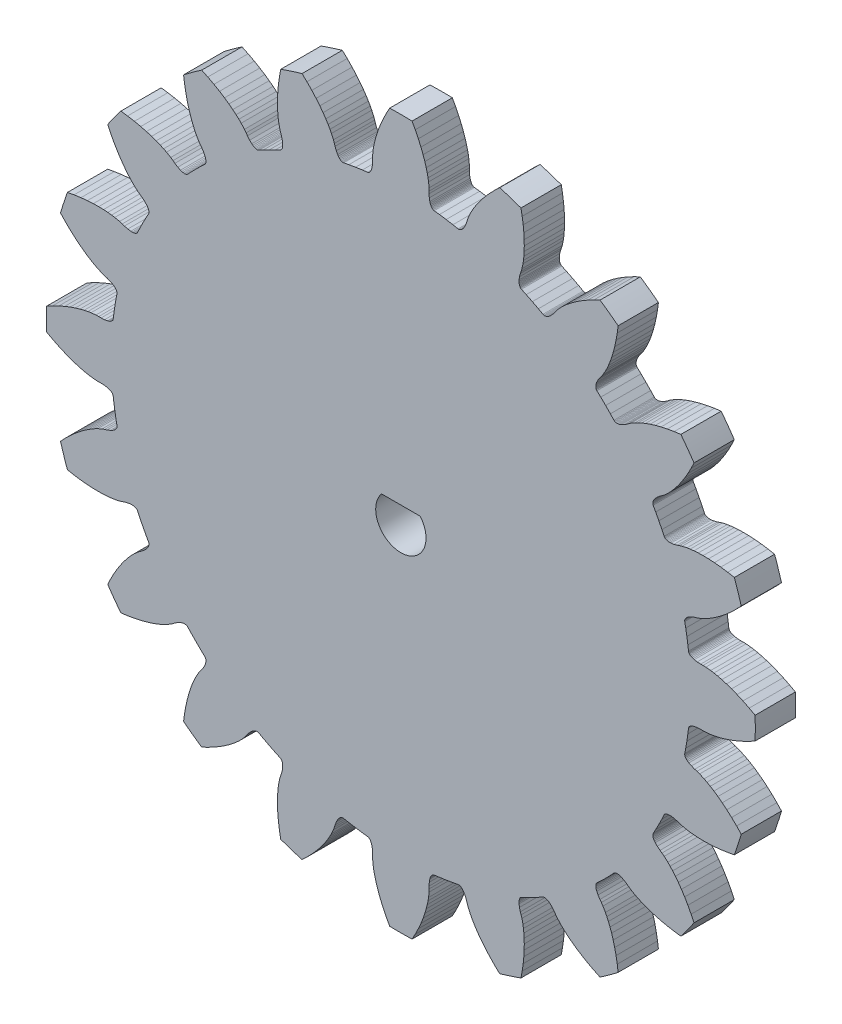
SolidWorks part; units mm, degrees
ref_plane "Front Plane" through (0, 0, 0) normal (0, 0, 1) x (1, 0, 0)
ref_plane "Top Plane" through (0, 0, 0) normal (0, 1, 0) x (1, 0, 0)
ref_plane "Right Plane" through (0, 0, 0) normal (1, 0, 0) x (0, 0, -1)
sketch "Model" plane through (0, 0, 0) normal (0, 0, 1) x (1, 0, 0)
  line L0 (41.6786, 11.6622) -> (41.0581, 11.0595)
  line L1 (41.0581, 11.0595) -> (40.4611, 10.5264)
  line L2 (40.4611, 10.5264) -> (39.8935, 10.0607)
  line L3 (39.8935, 10.0607) -> (39.3607, 9.6597)
  line L4 (39.3607, 9.6597) -> (38.8648, 9.3179)
  line L5 (38.8648, 9.3179) -> (38.4118, 9.033)
  line L6 (38.4118, 9.033) -> (38.0041, 8.7997)
  line L7 (38.0041, 8.7997) -> (37.6455, 8.6139)
  line L8 (37.6455, 8.6139) -> (37.0884, 8.3667)
  line L9 (37.0884, 8.3667) -> (36.7615, 8.2523)
  line L10 (36.7615, 8.2523) -> (36.4807, 8.1681)
  line L11 (36.4807, 8.1681) -> (36.0803, 8.0133)
  line L12 (36.0803, 8.0133) -> (35.757, 7.8422)
  line L13 (35.757, 7.8422) -> (35.6244, 7.7525)
  line L14 (35.6244, 7.7525) -> (35.5112, 7.661)
  line L15 (35.5112, 7.661) -> (35.4174, 7.5686)
  line L16 (35.4174, 7.5686) -> (35.3431, 7.476)
  line L17 (35.3431, 7.476) -> (35.2881, 7.3839)
  line L18 (35.2881, 7.3839) -> (35.2524, 7.2932)
  line L19 (35.2524, 7.2932) -> (35.236, 7.2046)
  line L20 (35.236, 7.2046) -> (35.2423, 7.0979)
  line L21 (35.2423, 7.0979) -> (35.3653, 6.4581)
  line L22 (35.3653, 6.4581) -> (35.5074, 5.6238)
  line L23 (35.5074, 5.6238) -> (35.6301, 4.7864)
  line L24 (35.6301, 4.7864) -> (35.7108, 4.1399)
  line L25 (35.7108, 4.1399) -> (35.7378, 4.0366)
  line L26 (35.7378, 4.0366) -> (35.7808, 3.9574)
  line L27 (35.7808, 3.9574) -> (35.8427, 3.8821)
  line L28 (35.8427, 3.8821) -> (35.9235, 3.8115)
  line L29 (35.9235, 3.8115) -> (36.0228, 3.7464)
  line L30 (36.0228, 3.7464) -> (36.1405, 3.6875)
  line L31 (36.1405, 3.6875) -> (36.2764, 3.6355)
  line L32 (36.2764, 3.6355) -> (36.4303, 3.5911)
  line L33 (36.4303, 3.5911) -> (36.7907, 3.5283)
  line L34 (36.7907, 3.5283) -> (37.2193, 3.5048)
  line L35 (37.2193, 3.5048) -> (37.5124, 3.5115)
  line L36 (37.5124, 3.5115) -> (37.8587, 3.5038)
  line L37 (37.8587, 3.5038) -> (38.4649, 3.4408)
  line L38 (38.4649, 3.4408) -> (38.8633, 3.3749)
  line L39 (38.8633, 3.3749) -> (39.3231, 3.279)
  line L40 (39.3231, 3.279) -> (39.842, 3.148)
  line L41 (39.842, 3.148) -> (40.4192, 2.9762)
  line L42 (40.4192, 2.9762) -> (41.0499, 2.7595)
  line L43 (41.0499, 2.7595) -> (41.7336, 2.492)
  line L44 (41.7336, 2.492) -> (42.4661, 2.1695)
  line L45 (42.4661, 2.1695) -> (43.2425, 1.788)
  line L46 (43.2425, 1.788) -> (43.978, 1.389)
  line L47 (43.978, -1.389) -> (43.2425, -1.788)
  line L48 (43.2425, -1.788) -> (42.4661, -2.1695)
  line L49 (42.4661, -2.1695) -> (41.7336, -2.492)
  line L50 (41.7336, -2.492) -> (41.0499, -2.7595)
  line L51 (41.0499, -2.7595) -> (40.4192, -2.9762)
  line L52 (40.4192, -2.9762) -> (39.842, -3.148)
  line L53 (39.842, -3.148) -> (39.3231, -3.279)
  line L54 (39.3231, -3.279) -> (38.8633, -3.3749)
  line L55 (38.8633, -3.3749) -> (38.4649, -3.4408)
  line L56 (38.4649, -3.4408) -> (37.8587, -3.5038)
  line L57 (37.8587, -3.5038) -> (37.5124, -3.5115)
  line L58 (37.5124, -3.5115) -> (37.2193, -3.5048)
  line L59 (37.2193, -3.5048) -> (36.7907, -3.5283)
  line L60 (36.7907, -3.5283) -> (36.4303, -3.5911)
  line L61 (36.4303, -3.5911) -> (36.2764, -3.6355)
  line L62 (36.2764, -3.6355) -> (36.1405, -3.6875)
  line L63 (36.1405, -3.6875) -> (36.0228, -3.7464)
  line L64 (36.0228, -3.7464) -> (35.9235, -3.8115)
  line L65 (35.9235, -3.8115) -> (35.8427, -3.8821)
  line L66 (35.8427, -3.8821) -> (35.7808, -3.9574)
  line L67 (35.7808, -3.9574) -> (35.7378, -4.0366)
  line L68 (35.7378, -4.0366) -> (35.7108, -4.1399)
  line L69 (35.7108, -4.1399) -> (35.6301, -4.7864)
  line L70 (35.6301, -4.7864) -> (35.5074, -5.6238)
  line L71 (35.5074, -5.6238) -> (35.3653, -6.4581)
  line L72 (35.3653, -6.4581) -> (35.2423, -7.0979)
  line L73 (35.2423, -7.0979) -> (35.236, -7.2046)
  line L74 (35.236, -7.2046) -> (35.2524, -7.2932)
  line L75 (35.2524, -7.2932) -> (35.2881, -7.3839)
  line L76 (35.2881, -7.3839) -> (35.3431, -7.476)
  line L77 (35.3431, -7.476) -> (35.4174, -7.5686)
  line L78 (35.4174, -7.5686) -> (35.5112, -7.661)
  line L79 (35.5112, -7.661) -> (35.6244, -7.7525)
  line L80 (35.6244, -7.7525) -> (35.757, -7.8422)
  line L81 (35.757, -7.8422) -> (36.0803, -8.0133)
  line L82 (36.0803, -8.0133) -> (36.4807, -8.1681)
  line L83 (36.4807, -8.1681) -> (36.7615, -8.2523)
  line L84 (36.7615, -8.2523) -> (37.0884, -8.3667)
  line L85 (37.0884, -8.3667) -> (37.6455, -8.6139)
  line L86 (37.6455, -8.6139) -> (38.0041, -8.7997)
  line L87 (38.0041, -8.7997) -> (38.4118, -9.033)
  line L88 (38.4118, -9.033) -> (38.8648, -9.3179)
  line L89 (38.8648, -9.3179) -> (39.3607, -9.6597)
  line L90 (39.3607, -9.6597) -> (39.8935, -10.0607)
  line L91 (39.8935, -10.0607) -> (40.4611, -10.5264)
  line L92 (40.4611, -10.5264) -> (41.0581, -11.0595)
  line L93 (41.0581, -11.0595) -> (41.6786, -11.6622)
  line L94 (41.6786, -11.6622) -> (42.2548, -12.2689)
  line L95 (41.3963, -14.911) -> (40.5736, -15.0632)
  line L96 (40.5736, -15.0632) -> (39.7173, -15.186)
  line L97 (39.7173, -15.186) -> (38.921, -15.2664)
  line L98 (38.921, -15.2664) -> (38.1881, -15.3095)
  line L99 (38.1881, -15.3095) -> (37.5212, -15.3208)
  line L100 (37.5212, -15.3208) -> (36.9192, -15.3058)
  line L101 (36.9192, -15.3058) -> (36.3852, -15.2701)
  line L102 (36.3852, -15.2701) -> (35.9183, -15.2192)
  line L103 (35.9183, -15.2192) -> (35.519, -15.1587)
  line L104 (35.519, -15.1587) -> (34.923, -15.0313)
  line L105 (34.923, -15.0313) -> (34.5913, -14.9316)
  line L106 (34.5913, -14.9316) -> (34.3146, -14.8347)
  line L107 (34.3146, -14.8347) -> (33.8997, -14.7246)
  line L108 (33.8997, -14.7246) -> (33.5375, -14.673)
  line L109 (33.5375, -14.673) -> (33.3775, -14.6676)
  line L110 (33.3775, -14.6676) -> (33.2322, -14.675)
  line L111 (33.2322, -14.675) -> (33.102, -14.6947)
  line L112 (33.102, -14.6947) -> (32.9874, -14.726)
  line L113 (32.9874, -14.726) -> (32.8888, -14.7681)
  line L114 (32.8888, -14.7681) -> (32.8066, -14.8206)
  line L115 (32.8066, -14.8206) -> (32.7413, -14.8826)
  line L116 (32.7413, -14.8826) -> (32.6837, -14.9726)
  line L117 (32.6837, -14.9726) -> (32.4071, -15.5625)
  line L118 (32.4071, -15.5625) -> (32.0317, -16.321)
  line L119 (32.0317, -16.321) -> (31.6387, -17.0705)
  line L120 (31.6387, -17.0705) -> (31.3241, -17.641)
  line L121 (31.3241, -17.641) -> (31.2851, -17.7405)
  line L122 (31.2851, -17.7405) -> (31.2733, -17.8298)
  line L123 (31.2733, -17.8298) -> (31.2792, -17.9271)
  line L124 (31.2792, -17.9271) -> (31.3031, -18.0317)
  line L125 (31.3031, -18.0317) -> (31.3451, -18.1427)
  line L126 (31.3451, -18.1427) -> (31.4057, -18.2596)
  line L127 (31.4057, -18.2596) -> (31.4851, -18.3816)
  line L128 (31.4851, -18.3816) -> (31.5835, -18.5079)
  line L129 (31.5835, -18.5079) -> (31.8382, -18.7705)
  line L130 (31.8382, -18.7705) -> (32.1711, -19.0415)
  line L131 (32.1711, -19.0415) -> (32.4121, -19.2084)
  line L132 (32.4121, -19.2084) -> (32.6878, -19.4181)
  line L133 (32.6878, -19.4181) -> (33.1412, -19.8254)
  line L134 (33.1412, -19.8254) -> (33.4248, -20.1129)
  line L135 (33.4248, -20.1129) -> (33.7404, -20.4607)
  line L136 (33.7404, -20.4607) -> (34.0832, -20.8718)
  line L137 (34.0832, -20.8718) -> (34.4492, -21.35)
  line L138 (34.4492, -21.35) -> (34.832, -21.8961)
  line L139 (34.832, -21.8961) -> (35.228, -22.5143)
  line L140 (35.228, -22.5143) -> (35.631, -23.2058)
  line L141 (35.631, -23.2058) -> (36.0349, -23.9708)
  line L142 (36.0349, -23.9708) -> (36.3954, -24.7259)
  line L143 (34.7625, -26.9734) -> (33.933, -26.8638)
  line L144 (33.933, -26.8638) -> (33.0806, -26.7161)
  line L145 (33.0806, -26.7161) -> (32.2984, -26.5465)
  line L146 (32.2984, -26.5465) -> (31.5881, -26.361)
  line L147 (31.5881, -26.361) -> (30.9504, -26.1656)
  line L148 (30.9504, -26.1656) -> (30.3825, -25.9653)
  line L149 (30.3825, -25.9653) -> (29.8857, -25.7663)
  line L150 (29.8857, -25.7663) -> (29.4573, -25.5736)
  line L151 (29.4573, -25.5736) -> (29.0963, -25.3927)
  line L152 (29.0963, -25.3927) -> (28.5688, -25.0874)
  line L153 (28.5688, -25.0874) -> (28.2841, -24.8901)
  line L154 (28.2841, -24.8901) -> (28.0509, -24.7124)
  line L155 (28.0509, -24.7124) -> (27.6904, -24.4795)
  line L156 (27.6904, -24.4795) -> (27.3619, -24.3185)
  line L157 (27.3619, -24.3185) -> (27.2114, -24.2639)
  line L158 (27.2114, -24.2639) -> (27.0708, -24.2261)
  line L159 (27.0708, -24.2261) -> (26.941, -24.2046)
  line L160 (26.941, -24.2046) -> (26.8223, -24.1989)
  line L161 (26.8223, -24.1989) -> (26.7155, -24.2085)
  line L162 (26.7155, -24.2085) -> (26.6212, -24.233)
  line L163 (26.6212, -24.233) -> (26.5398, -24.2718)
  line L164 (26.5398, -24.2718) -> (26.4573, -24.3396)
  line L165 (26.4573, -24.3396) -> (26.0119, -24.8151)
  line L166 (26.0119, -24.8151) -> (25.4205, -25.4205)
  line L167 (25.4205, -25.4205) -> (24.8151, -26.0119)
  line L168 (24.8151, -26.0119) -> (24.3396, -26.4573)
  line L169 (24.3396, -26.4573) -> (24.2718, -26.5398)
  line L170 (24.2718, -26.5398) -> (24.233, -26.6212)
  line L171 (24.233, -26.6212) -> (24.2085, -26.7155)
  line L172 (24.2085, -26.7155) -> (24.1989, -26.8223)
  line L173 (24.1989, -26.8223) -> (24.2046, -26.941)
  line L174 (24.2046, -26.941) -> (24.2261, -27.0708)
  line L175 (24.2261, -27.0708) -> (24.2639, -27.2114)
  line L176 (24.2639, -27.2114) -> (24.3185, -27.3619)
  line L177 (24.3185, -27.3619) -> (24.4795, -27.6904)
  line L178 (24.4795, -27.6904) -> (24.7124, -28.0509)
  line L179 (24.7124, -28.0509) -> (24.8901, -28.2841)
  line L180 (24.8901, -28.2841) -> (25.0874, -28.5688)
  line L181 (25.0874, -28.5688) -> (25.3927, -29.0963)
  line L182 (25.3927, -29.0963) -> (25.5736, -29.4573)
  line L183 (25.5736, -29.4573) -> (25.7663, -29.8857)
  line L184 (25.7663, -29.8857) -> (25.9653, -30.3825)
  line L185 (25.9653, -30.3825) -> (26.1656, -30.9504)
  line L186 (26.1656, -30.9504) -> (26.361, -31.5881)
  line L187 (26.361, -31.5881) -> (26.5465, -32.2984)
  line L188 (26.5465, -32.2984) -> (26.7161, -33.0806)
  line L189 (26.7161, -33.0806) -> (26.8638, -33.933)
  line L190 (26.8638, -33.933) -> (26.9734, -34.7625)
  line L191 (24.7259, -36.3954) -> (23.9708, -36.0349)
  line L192 (23.9708, -36.0349) -> (23.2058, -35.631)
  line L193 (23.2058, -35.631) -> (22.5143, -35.228)
  line L194 (22.5143, -35.228) -> (21.8961, -34.832)
  line L195 (21.8961, -34.832) -> (21.35, -34.4492)
  line L196 (21.35, -34.4492) -> (20.8718, -34.0832)
  line L197 (20.8718, -34.0832) -> (20.4607, -33.7404)
  line L198 (20.4607, -33.7404) -> (20.1129, -33.4248)
  line L199 (20.1129, -33.4248) -> (19.8254, -33.1412)
  line L200 (19.8254, -33.1412) -> (19.4181, -32.6878)
  line L201 (19.4181, -32.6878) -> (19.2084, -32.4121)
  line L202 (19.2084, -32.4121) -> (19.0415, -32.1711)
  line L203 (19.0415, -32.1711) -> (18.7705, -31.8382)
  line L204 (18.7705, -31.8382) -> (18.5079, -31.5835)
  line L205 (18.5079, -31.5835) -> (18.3816, -31.4851)
  line L206 (18.3816, -31.4851) -> (18.2596, -31.4057)
  line L207 (18.2596, -31.4057) -> (18.1427, -31.3451)
  line L208 (18.1427, -31.3451) -> (18.0317, -31.3031)
  line L209 (18.0317, -31.3031) -> (17.9271, -31.2792)
  line L210 (17.9271, -31.2792) -> (17.8298, -31.2733)
  line L211 (17.8298, -31.2733) -> (17.7405, -31.2851)
  line L212 (17.7405, -31.2851) -> (17.641, -31.3241)
  line L213 (17.641, -31.3241) -> (17.0705, -31.6387)
  line L214 (17.0705, -31.6387) -> (16.321, -32.0317)
  line L215 (16.321, -32.0317) -> (15.5625, -32.4071)
  line L216 (15.5625, -32.4071) -> (14.9726, -32.6837)
  line L217 (14.9726, -32.6837) -> (14.8826, -32.7413)
  line L218 (14.8826, -32.7413) -> (14.8206, -32.8066)
  line L219 (14.8206, -32.8066) -> (14.7681, -32.8888)
  line L220 (14.7681, -32.8888) -> (14.726, -32.9874)
  line L221 (14.726, -32.9874) -> (14.6947, -33.102)
  line L222 (14.6947, -33.102) -> (14.675, -33.2322)
  line L223 (14.675, -33.2322) -> (14.6676, -33.3775)
  line L224 (14.6676, -33.3775) -> (14.673, -33.5375)
  line L225 (14.673, -33.5375) -> (14.7246, -33.8997)
  line L226 (14.7246, -33.8997) -> (14.8347, -34.3146)
  line L227 (14.8347, -34.3146) -> (14.9316, -34.5913)
  line L228 (14.9316, -34.5913) -> (15.0313, -34.923)
  line L229 (15.0313, -34.923) -> (15.1587, -35.519)
  line L230 (15.1587, -35.519) -> (15.2192, -35.9183)
  line L231 (15.2192, -35.9183) -> (15.2701, -36.3852)
  line L232 (15.2701, -36.3852) -> (15.3058, -36.9192)
  line L233 (15.3058, -36.9192) -> (15.3208, -37.5212)
  line L234 (15.3208, -37.5212) -> (15.3095, -38.1881)
  line L235 (15.3095, -38.1881) -> (15.2664, -38.921)
  line L236 (15.2664, -38.921) -> (15.186, -39.7173)
  line L237 (15.186, -39.7173) -> (15.0632, -40.5736)
  line L238 (15.0632, -40.5736) -> (14.911, -41.3963)
  line L239 (12.2689, -42.2548) -> (11.6622, -41.6786)
  line L240 (11.6622, -41.6786) -> (11.0595, -41.0581)
  line L241 (11.0595, -41.0581) -> (10.5264, -40.4611)
  line L242 (10.5264, -40.4611) -> (10.0607, -39.8935)
  line L243 (10.0607, -39.8935) -> (9.6597, -39.3607)
  line L244 (9.6597, -39.3607) -> (9.3179, -38.8648)
  line L245 (9.3179, -38.8648) -> (9.033, -38.4118)
  line L246 (9.033, -38.4118) -> (8.7997, -38.0041)
  line L247 (8.7997, -38.0041) -> (8.6139, -37.6455)
  line L248 (8.6139, -37.6455) -> (8.3667, -37.0884)
  line L249 (8.3667, -37.0884) -> (8.2523, -36.7615)
  line L250 (8.2523, -36.7615) -> (8.1681, -36.4807)
  line L251 (8.1681, -36.4807) -> (8.0133, -36.0803)
  line L252 (8.0133, -36.0803) -> (7.8422, -35.757)
  line L253 (7.8422, -35.757) -> (7.7525, -35.6244)
  line L254 (7.7525, -35.6244) -> (7.661, -35.5112)
  line L255 (7.661, -35.5112) -> (7.5686, -35.4174)
  line L256 (7.5686, -35.4174) -> (7.476, -35.3431)
  line L257 (7.476, -35.3431) -> (7.3839, -35.2881)
  line L258 (7.3839, -35.2881) -> (7.2932, -35.2524)
  line L259 (7.2932, -35.2524) -> (7.2046, -35.236)
  line L260 (7.2046, -35.236) -> (7.0979, -35.2423)
  line L261 (7.0979, -35.2423) -> (6.4581, -35.3653)
  line L262 (6.4581, -35.3653) -> (5.6238, -35.5074)
  line L263 (5.6238, -35.5074) -> (4.7864, -35.6301)
  line L264 (4.7864, -35.6301) -> (4.1399, -35.7108)
  line L265 (4.1399, -35.7108) -> (4.0366, -35.7378)
  line L266 (4.0366, -35.7378) -> (3.9574, -35.7808)
  line L267 (3.9574, -35.7808) -> (3.8821, -35.8427)
  line L268 (3.8821, -35.8427) -> (3.8115, -35.9235)
  line L269 (3.8115, -35.9235) -> (3.7464, -36.0228)
  line L270 (3.7464, -36.0228) -> (3.6875, -36.1405)
  line L271 (3.6875, -36.1405) -> (3.6355, -36.2764)
  line L272 (3.6355, -36.2764) -> (3.5911, -36.4303)
  line L273 (3.5911, -36.4303) -> (3.5283, -36.7907)
  line L274 (3.5283, -36.7907) -> (3.5048, -37.2193)
  line L275 (3.5048, -37.2193) -> (3.5115, -37.5124)
  line L276 (3.5115, -37.5124) -> (3.5038, -37.8587)
  line L277 (3.5038, -37.8587) -> (3.4408, -38.4649)
  line L278 (3.4408, -38.4649) -> (3.3749, -38.8633)
  line L279 (3.3749, -38.8633) -> (3.279, -39.3231)
  line L280 (3.279, -39.3231) -> (3.148, -39.842)
  line L281 (3.148, -39.842) -> (2.9762, -40.4192)
  line L282 (2.9762, -40.4192) -> (2.7595, -41.0499)
  line L283 (2.7595, -41.0499) -> (2.492, -41.7336)
  line L284 (2.492, -41.7336) -> (2.1695, -42.4661)
  line L285 (2.1695, -42.4661) -> (1.788, -43.2425)
  line L286 (1.788, -43.2425) -> (1.389, -43.978)
  line L287 (-1.389, -43.978) -> (-1.788, -43.2425)
  line L288 (-1.788, -43.2425) -> (-2.1695, -42.4661)
  line L289 (-2.1695, -42.4661) -> (-2.492, -41.7336)
  line L290 (-2.492, -41.7336) -> (-2.7595, -41.0499)
  line L291 (-2.7595, -41.0499) -> (-2.9762, -40.4192)
  line L292 (-2.9762, -40.4192) -> (-3.148, -39.842)
  line L293 (-3.148, -39.842) -> (-3.279, -39.3231)
  line L294 (-3.279, -39.3231) -> (-3.3749, -38.8633)
  line L295 (-3.3749, -38.8633) -> (-3.4408, -38.4649)
  line L296 (-3.4408, -38.4649) -> (-3.5038, -37.8587)
  line L297 (-3.5038, -37.8587) -> (-3.5115, -37.5124)
  line L298 (-3.5115, -37.5124) -> (-3.5048, -37.2193)
  line L299 (-3.5048, -37.2193) -> (-3.5283, -36.7907)
  line L300 (-3.5283, -36.7907) -> (-3.5911, -36.4303)
  line L301 (-3.5911, -36.4303) -> (-3.6355, -36.2764)
  line L302 (-3.6355, -36.2764) -> (-3.6875, -36.1405)
  line L303 (-3.6875, -36.1405) -> (-3.7464, -36.0228)
  line L304 (-3.7464, -36.0228) -> (-3.8115, -35.9235)
  line L305 (-3.8115, -35.9235) -> (-3.8821, -35.8427)
  line L306 (-3.8821, -35.8427) -> (-3.9574, -35.7808)
  line L307 (-3.9574, -35.7808) -> (-4.0366, -35.7378)
  line L308 (-4.0366, -35.7378) -> (-4.1399, -35.7108)
  line L309 (-4.1399, -35.7108) -> (-4.7864, -35.6301)
  line L310 (-4.7864, -35.6301) -> (-5.6238, -35.5074)
  line L311 (-5.6238, -35.5074) -> (-6.4581, -35.3653)
  line L312 (-6.4581, -35.3653) -> (-7.0979, -35.2423)
  line L313 (-7.0979, -35.2423) -> (-7.2046, -35.236)
  line L314 (-7.2046, -35.236) -> (-7.2932, -35.2524)
  line L315 (-7.2932, -35.2524) -> (-7.3839, -35.2881)
  line L316 (-7.3839, -35.2881) -> (-7.476, -35.3431)
  line L317 (-7.476, -35.3431) -> (-7.5686, -35.4174)
  line L318 (-7.5686, -35.4174) -> (-7.661, -35.5112)
  line L319 (-7.661, -35.5112) -> (-7.7525, -35.6244)
  line L320 (-7.7525, -35.6244) -> (-7.8422, -35.757)
  line L321 (-7.8422, -35.757) -> (-8.0133, -36.0803)
  line L322 (-8.0133, -36.0803) -> (-8.1681, -36.4807)
  line L323 (-8.1681, -36.4807) -> (-8.2523, -36.7615)
  line L324 (-8.2523, -36.7615) -> (-8.3667, -37.0884)
  line L325 (-8.3667, -37.0884) -> (-8.6139, -37.6455)
  line L326 (-8.6139, -37.6455) -> (-8.7997, -38.0041)
  line L327 (-8.7997, -38.0041) -> (-9.033, -38.4118)
  line L328 (-9.033, -38.4118) -> (-9.3179, -38.8648)
  line L329 (-9.3179, -38.8648) -> (-9.6597, -39.3607)
  line L330 (-9.6597, -39.3607) -> (-10.0607, -39.8935)
  line L331 (-10.0607, -39.8935) -> (-10.5264, -40.4611)
  line L332 (-10.5264, -40.4611) -> (-11.0595, -41.0581)
  line L333 (-11.0595, -41.0581) -> (-11.6622, -41.6786)
  line L334 (-11.6622, -41.6786) -> (-12.2689, -42.2548)
  line L335 (-14.911, -41.3963) -> (-15.0632, -40.5736)
  line L336 (-15.0632, -40.5736) -> (-15.186, -39.7173)
  line L337 (-15.186, -39.7173) -> (-15.2664, -38.921)
  line L338 (-15.2664, -38.921) -> (-15.3095, -38.1881)
  line L339 (-15.3095, -38.1881) -> (-15.3208, -37.5212)
  line L340 (-15.3208, -37.5212) -> (-15.3058, -36.9192)
  line L341 (-15.3058, -36.9192) -> (-15.2701, -36.3852)
  line L342 (-15.2701, -36.3852) -> (-15.2192, -35.9183)
  line L343 (-15.2192, -35.9183) -> (-15.1587, -35.519)
  line L344 (-15.1587, -35.519) -> (-15.0313, -34.923)
  line L345 (-15.0313, -34.923) -> (-14.9316, -34.5913)
  line L346 (-14.9316, -34.5913) -> (-14.8347, -34.3146)
  line L347 (-14.8347, -34.3146) -> (-14.7246, -33.8997)
  line L348 (-14.7246, -33.8997) -> (-14.673, -33.5375)
  line L349 (-14.673, -33.5375) -> (-14.6676, -33.3775)
  line L350 (-14.6676, -33.3775) -> (-14.675, -33.2322)
  line L351 (-14.675, -33.2322) -> (-14.6947, -33.102)
  line L352 (-14.6947, -33.102) -> (-14.726, -32.9874)
  line L353 (-14.726, -32.9874) -> (-14.7681, -32.8888)
  line L354 (-14.7681, -32.8888) -> (-14.8206, -32.8066)
  line L355 (-14.8206, -32.8066) -> (-14.8826, -32.7413)
  line L356 (-14.8826, -32.7413) -> (-14.9726, -32.6837)
  line L357 (-14.9726, -32.6837) -> (-15.5625, -32.4071)
  line L358 (-15.5625, -32.4071) -> (-16.321, -32.0317)
  line L359 (-16.321, -32.0317) -> (-17.0705, -31.6387)
  line L360 (-17.0705, -31.6387) -> (-17.641, -31.3241)
  line L361 (-17.641, -31.3241) -> (-17.7405, -31.2851)
  line L362 (-17.7405, -31.2851) -> (-17.8298, -31.2733)
  line L363 (-17.8298, -31.2733) -> (-17.9271, -31.2792)
  line L364 (-17.9271, -31.2792) -> (-18.0317, -31.3031)
  line L365 (-18.0317, -31.3031) -> (-18.1427, -31.3451)
  line L366 (-18.1427, -31.3451) -> (-18.2596, -31.4057)
  line L367 (-18.2596, -31.4057) -> (-18.3816, -31.4851)
  line L368 (-18.3816, -31.4851) -> (-18.5079, -31.5835)
  line L369 (-18.5079, -31.5835) -> (-18.7705, -31.8382)
  line L370 (-18.7705, -31.8382) -> (-19.0415, -32.1711)
  line L371 (-19.0415, -32.1711) -> (-19.2084, -32.4121)
  line L372 (-19.2084, -32.4121) -> (-19.4181, -32.6878)
  line L373 (-19.4181, -32.6878) -> (-19.8254, -33.1412)
  line L374 (-19.8254, -33.1412) -> (-20.1129, -33.4248)
  line L375 (-20.1129, -33.4248) -> (-20.4607, -33.7404)
  line L376 (-20.4607, -33.7404) -> (-20.8718, -34.0832)
  line L377 (-20.8718, -34.0832) -> (-21.35, -34.4492)
  line L378 (-21.35, -34.4492) -> (-21.8961, -34.832)
  line L379 (-21.8961, -34.832) -> (-22.5143, -35.228)
  line L380 (-22.5143, -35.228) -> (-23.2058, -35.631)
  line L381 (-23.2058, -35.631) -> (-23.9708, -36.0349)
  line L382 (-23.9708, -36.0349) -> (-24.7259, -36.3954)
  line L383 (-26.9734, -34.7625) -> (-26.8638, -33.933)
  line L384 (-26.8638, -33.933) -> (-26.7161, -33.0806)
  line L385 (-26.7161, -33.0806) -> (-26.5465, -32.2984)
  line L386 (-26.5465, -32.2984) -> (-26.361, -31.5881)
  line L387 (-26.361, -31.5881) -> (-26.1656, -30.9504)
  line L388 (-26.1656, -30.9504) -> (-25.9653, -30.3825)
  line L389 (-25.9653, -30.3825) -> (-25.7663, -29.8857)
  line L390 (-25.7663, -29.8857) -> (-25.5736, -29.4573)
  line L391 (-25.5736, -29.4573) -> (-25.3927, -29.0963)
  line L392 (-25.3927, -29.0963) -> (-25.0874, -28.5688)
  line L393 (-25.0874, -28.5688) -> (-24.8901, -28.2841)
  line L394 (-24.8901, -28.2841) -> (-24.7124, -28.0509)
  line L395 (-24.7124, -28.0509) -> (-24.4795, -27.6904)
  line L396 (-24.4795, -27.6904) -> (-24.3185, -27.3619)
  line L397 (-24.3185, -27.3619) -> (-24.2639, -27.2114)
  line L398 (-24.2639, -27.2114) -> (-24.2261, -27.0708)
  line L399 (-24.2261, -27.0708) -> (-24.2046, -26.941)
  line L400 (-24.2046, -26.941) -> (-24.1989, -26.8223)
  line L401 (-24.1989, -26.8223) -> (-24.2085, -26.7155)
  line L402 (-24.2085, -26.7155) -> (-24.233, -26.6212)
  line L403 (-24.233, -26.6212) -> (-24.2718, -26.5398)
  line L404 (-24.2718, -26.5398) -> (-24.3396, -26.4573)
  line L405 (-24.3396, -26.4573) -> (-24.8151, -26.0119)
  line L406 (-24.8151, -26.0119) -> (-25.4205, -25.4205)
  line L407 (-25.4205, -25.4205) -> (-26.0119, -24.8151)
  line L408 (-26.0119, -24.8151) -> (-26.4573, -24.3396)
  line L409 (-26.4573, -24.3396) -> (-26.5398, -24.2718)
  line L410 (-26.5398, -24.2718) -> (-26.6212, -24.233)
  line L411 (-26.6212, -24.233) -> (-26.7155, -24.2085)
  line L412 (-26.7155, -24.2085) -> (-26.8223, -24.1989)
  line L413 (-26.8223, -24.1989) -> (-26.941, -24.2046)
  line L414 (-26.941, -24.2046) -> (-27.0708, -24.2261)
  line L415 (-27.0708, -24.2261) -> (-27.2114, -24.2639)
  line L416 (-27.2114, -24.2639) -> (-27.3619, -24.3185)
  line L417 (-27.3619, -24.3185) -> (-27.6904, -24.4795)
  line L418 (-27.6904, -24.4795) -> (-28.0509, -24.7124)
  line L419 (-28.0509, -24.7124) -> (-28.2841, -24.8901)
  line L420 (-28.2841, -24.8901) -> (-28.5688, -25.0874)
  line L421 (-28.5688, -25.0874) -> (-29.0963, -25.3927)
  line L422 (-29.0963, -25.3927) -> (-29.4573, -25.5736)
  line L423 (-29.4573, -25.5736) -> (-29.8857, -25.7663)
  line L424 (-29.8857, -25.7663) -> (-30.3825, -25.9653)
  line L425 (-30.3825, -25.9653) -> (-30.9504, -26.1656)
  line L426 (-30.9504, -26.1656) -> (-31.5881, -26.361)
  line L427 (-31.5881, -26.361) -> (-32.2984, -26.5465)
  line L428 (-32.2984, -26.5465) -> (-33.0806, -26.7161)
  line L429 (-33.0806, -26.7161) -> (-33.933, -26.8638)
  line L430 (-33.933, -26.8638) -> (-34.7625, -26.9734)
  line L431 (-36.3954, -24.7259) -> (-36.0349, -23.9708)
  line L432 (-36.0349, -23.9708) -> (-35.631, -23.2058)
  line L433 (-35.631, -23.2058) -> (-35.228, -22.5143)
  line L434 (-35.228, -22.5143) -> (-34.832, -21.8961)
  line L435 (-34.832, -21.8961) -> (-34.4492, -21.35)
  line L436 (-34.4492, -21.35) -> (-34.0832, -20.8718)
  line L437 (-34.0832, -20.8718) -> (-33.7404, -20.4607)
  line L438 (-33.7404, -20.4607) -> (-33.4248, -20.1129)
  line L439 (-33.4248, -20.1129) -> (-33.1412, -19.8254)
  line L440 (-33.1412, -19.8254) -> (-32.6878, -19.4181)
  line L441 (-32.6878, -19.4181) -> (-32.4121, -19.2084)
  line L442 (-32.4121, -19.2084) -> (-32.1711, -19.0415)
  line L443 (-32.1711, -19.0415) -> (-31.8382, -18.7705)
  line L444 (-31.8382, -18.7705) -> (-31.5835, -18.5079)
  line L445 (-31.5835, -18.5079) -> (-31.4851, -18.3816)
  line L446 (-31.4851, -18.3816) -> (-31.4057, -18.2596)
  line L447 (-31.4057, -18.2596) -> (-31.3451, -18.1427)
  line L448 (-31.3451, -18.1427) -> (-31.3031, -18.0317)
  line L449 (-31.3031, -18.0317) -> (-31.2792, -17.9271)
  line L450 (-31.2792, -17.9271) -> (-31.2733, -17.8298)
  line L451 (-31.2733, -17.8298) -> (-31.2851, -17.7405)
  line L452 (-31.2851, -17.7405) -> (-31.3241, -17.641)
  line L453 (-31.3241, -17.641) -> (-31.6387, -17.0705)
  line L454 (-31.6387, -17.0705) -> (-32.0317, -16.321)
  line L455 (-32.0317, -16.321) -> (-32.4071, -15.5625)
  line L456 (-32.4071, -15.5625) -> (-32.6837, -14.9726)
  line L457 (-32.6837, -14.9726) -> (-32.7413, -14.8826)
  line L458 (-32.7413, -14.8826) -> (-32.8066, -14.8206)
  line L459 (-32.8066, -14.8206) -> (-32.8888, -14.7681)
  line L460 (-32.8888, -14.7681) -> (-32.9874, -14.726)
  line L461 (-32.9874, -14.726) -> (-33.102, -14.6947)
  line L462 (-33.102, -14.6947) -> (-33.2322, -14.675)
  line L463 (-33.2322, -14.675) -> (-33.3775, -14.6676)
  line L464 (-33.3775, -14.6676) -> (-33.5375, -14.673)
  line L465 (-33.5375, -14.673) -> (-33.8997, -14.7246)
  line L466 (-33.8997, -14.7246) -> (-34.3146, -14.8347)
  line L467 (-34.3146, -14.8347) -> (-34.5913, -14.9316)
  line L468 (-34.5913, -14.9316) -> (-34.923, -15.0313)
  line L469 (-34.923, -15.0313) -> (-35.519, -15.1587)
  line L470 (-35.519, -15.1587) -> (-35.9183, -15.2192)
  line L471 (-35.9183, -15.2192) -> (-36.3852, -15.2701)
  line L472 (-36.3852, -15.2701) -> (-36.9192, -15.3058)
  line L473 (-36.9192, -15.3058) -> (-37.5212, -15.3208)
  line L474 (-37.5212, -15.3208) -> (-38.1881, -15.3095)
  line L475 (-38.1881, -15.3095) -> (-38.921, -15.2664)
  line L476 (-38.921, -15.2664) -> (-39.7173, -15.186)
  line L477 (-39.7173, -15.186) -> (-40.5736, -15.0632)
  line L478 (-40.5736, -15.0632) -> (-41.3963, -14.911)
  line L479 (-42.2548, -12.2689) -> (-41.6786, -11.6622)
  line L480 (-41.6786, -11.6622) -> (-41.0581, -11.0595)
  line L481 (-41.0581, -11.0595) -> (-40.4611, -10.5264)
  line L482 (-40.4611, -10.5264) -> (-39.8935, -10.0607)
  line L483 (-39.8935, -10.0607) -> (-39.3607, -9.6597)
  line L484 (-39.3607, -9.6597) -> (-38.8648, -9.3179)
  line L485 (-38.8648, -9.3179) -> (-38.4118, -9.033)
  line L486 (-38.4118, -9.033) -> (-38.0041, -8.7997)
  line L487 (-38.0041, -8.7997) -> (-37.6455, -8.6139)
  line L488 (-37.6455, -8.6139) -> (-37.0884, -8.3667)
  line L489 (-37.0884, -8.3667) -> (-36.7615, -8.2523)
  line L490 (-36.7615, -8.2523) -> (-36.4807, -8.1681)
  line L491 (-36.4807, -8.1681) -> (-36.0803, -8.0133)
  line L492 (-36.0803, -8.0133) -> (-35.757, -7.8422)
  line L493 (-35.757, -7.8422) -> (-35.6244, -7.7525)
  line L494 (-35.6244, -7.7525) -> (-35.5112, -7.661)
  line L495 (-35.5112, -7.661) -> (-35.4174, -7.5686)
  line L496 (-35.4174, -7.5686) -> (-35.3431, -7.476)
  line L497 (-35.3431, -7.476) -> (-35.2881, -7.3839)
  line L498 (-35.2881, -7.3839) -> (-35.2524, -7.2932)
  line L499 (-35.2524, -7.2932) -> (-35.236, -7.2046)
  line L500 (-35.236, -7.2046) -> (-35.2423, -7.0979)
  line L501 (-35.2423, -7.0979) -> (-35.3653, -6.4581)
  line L502 (-35.3653, -6.4581) -> (-35.5074, -5.6238)
  line L503 (-35.5074, -5.6238) -> (-35.6301, -4.7864)
  line L504 (-35.6301, -4.7864) -> (-35.7108, -4.1399)
  line L505 (-35.7108, -4.1399) -> (-35.7378, -4.0366)
  line L506 (-35.7378, -4.0366) -> (-35.7808, -3.9574)
  line L507 (-35.7808, -3.9574) -> (-35.8427, -3.8821)
  line L508 (-35.8427, -3.8821) -> (-35.9235, -3.8115)
  line L509 (-35.9235, -3.8115) -> (-36.0228, -3.7464)
  line L510 (-36.0228, -3.7464) -> (-36.1405, -3.6875)
  line L511 (-36.1405, -3.6875) -> (-36.2764, -3.6355)
  line L512 (-36.2764, -3.6355) -> (-36.4303, -3.5911)
  line L513 (-36.4303, -3.5911) -> (-36.7907, -3.5283)
  line L514 (-36.7907, -3.5283) -> (-37.2193, -3.5048)
  line L515 (-37.2193, -3.5048) -> (-37.5124, -3.5115)
  line L516 (-37.5124, -3.5115) -> (-37.8587, -3.5038)
  line L517 (-37.8587, -3.5038) -> (-38.4649, -3.4408)
  line L518 (-38.4649, -3.4408) -> (-38.8633, -3.3749)
  line L519 (-38.8633, -3.3749) -> (-39.3231, -3.279)
  line L520 (-39.3231, -3.279) -> (-39.842, -3.148)
  line L521 (-39.842, -3.148) -> (-40.4192, -2.9762)
  line L522 (-40.4192, -2.9762) -> (-41.0499, -2.7595)
  line L523 (-41.0499, -2.7595) -> (-41.7336, -2.492)
  line L524 (-41.7336, -2.492) -> (-42.4661, -2.1695)
  line L525 (-42.4661, -2.1695) -> (-43.2425, -1.788)
  line L526 (-43.2425, -1.788) -> (-43.978, -1.389)
  line L527 (-43.978, 1.389) -> (-43.2425, 1.788)
  line L528 (-43.2425, 1.788) -> (-42.4661, 2.1695)
  line L529 (-42.4661, 2.1695) -> (-41.7336, 2.492)
  line L530 (-41.7336, 2.492) -> (-41.0499, 2.7595)
  line L531 (-41.0499, 2.7595) -> (-40.4192, 2.9762)
  line L532 (-40.4192, 2.9762) -> (-39.842, 3.148)
  line L533 (-39.842, 3.148) -> (-39.3231, 3.279)
  line L534 (-39.3231, 3.279) -> (-38.8633, 3.3749)
  line L535 (-38.8633, 3.3749) -> (-38.4649, 3.4408)
  line L536 (-38.4649, 3.4408) -> (-37.8587, 3.5038)
  line L537 (-37.8587, 3.5038) -> (-37.5124, 3.5115)
  line L538 (-37.5124, 3.5115) -> (-37.2193, 3.5048)
  line L539 (-37.2193, 3.5048) -> (-36.7907, 3.5283)
  line L540 (-36.7907, 3.5283) -> (-36.4303, 3.5911)
  line L541 (-36.4303, 3.5911) -> (-36.2764, 3.6355)
  line L542 (-36.2764, 3.6355) -> (-36.1405, 3.6875)
  line L543 (-36.1405, 3.6875) -> (-36.0228, 3.7464)
  line L544 (-36.0228, 3.7464) -> (-35.9235, 3.8115)
  line L545 (-35.9235, 3.8115) -> (-35.8427, 3.8821)
  line L546 (-35.8427, 3.8821) -> (-35.7808, 3.9574)
  line L547 (-35.7808, 3.9574) -> (-35.7378, 4.0366)
  line L548 (-35.7378, 4.0366) -> (-35.7108, 4.1399)
  line L549 (-35.7108, 4.1399) -> (-35.6301, 4.7864)
  line L550 (-35.6301, 4.7864) -> (-35.5074, 5.6238)
  line L551 (-35.5074, 5.6238) -> (-35.3653, 6.4581)
  line L552 (-35.3653, 6.4581) -> (-35.2423, 7.0979)
  line L553 (-35.2423, 7.0979) -> (-35.236, 7.2046)
  line L554 (-35.236, 7.2046) -> (-35.2524, 7.2932)
  line L555 (-35.2524, 7.2932) -> (-35.2881, 7.3839)
  line L556 (-35.2881, 7.3839) -> (-35.3431, 7.476)
  line L557 (-35.3431, 7.476) -> (-35.4174, 7.5686)
  line L558 (-35.4174, 7.5686) -> (-35.5112, 7.661)
  line L559 (-35.5112, 7.661) -> (-35.6244, 7.7525)
  line L560 (-35.6244, 7.7525) -> (-35.757, 7.8422)
  line L561 (-35.757, 7.8422) -> (-36.0803, 8.0133)
  line L562 (-36.0803, 8.0133) -> (-36.4807, 8.1681)
  line L563 (-36.4807, 8.1681) -> (-36.7615, 8.2523)
  line L564 (-36.7615, 8.2523) -> (-37.0884, 8.3667)
  line L565 (-37.0884, 8.3667) -> (-37.6455, 8.6139)
  line L566 (-37.6455, 8.6139) -> (-38.0041, 8.7997)
  line L567 (-38.0041, 8.7997) -> (-38.4118, 9.033)
  line L568 (-38.4118, 9.033) -> (-38.8648, 9.3179)
  line L569 (-38.8648, 9.3179) -> (-39.3607, 9.6597)
  line L570 (-39.3607, 9.6597) -> (-39.8935, 10.0607)
  line L571 (-39.8935, 10.0607) -> (-40.4611, 10.5264)
  line L572 (-40.4611, 10.5264) -> (-41.0581, 11.0595)
  line L573 (-41.0581, 11.0595) -> (-41.6786, 11.6622)
  line L574 (-41.6786, 11.6622) -> (-42.2548, 12.2689)
  line L575 (-41.3963, 14.911) -> (-40.5736, 15.0632)
  line L576 (-40.5736, 15.0632) -> (-39.7173, 15.186)
  line L577 (-39.7173, 15.186) -> (-38.921, 15.2664)
  line L578 (-38.921, 15.2664) -> (-38.1881, 15.3095)
  line L579 (-38.1881, 15.3095) -> (-37.5212, 15.3208)
  line L580 (-37.5212, 15.3208) -> (-36.9192, 15.3058)
  line L581 (-36.9192, 15.3058) -> (-36.3852, 15.2701)
  line L582 (-36.3852, 15.2701) -> (-35.9183, 15.2192)
  line L583 (-35.9183, 15.2192) -> (-35.519, 15.1587)
  line L584 (-35.519, 15.1587) -> (-34.923, 15.0313)
  line L585 (-34.923, 15.0313) -> (-34.5913, 14.9316)
  line L586 (-34.5913, 14.9316) -> (-34.3146, 14.8347)
  line L587 (-34.3146, 14.8347) -> (-33.8997, 14.7246)
  line L588 (-33.8997, 14.7246) -> (-33.5375, 14.673)
  line L589 (-33.5375, 14.673) -> (-33.3775, 14.6676)
  line L590 (-33.3775, 14.6676) -> (-33.2322, 14.675)
  line L591 (-33.2322, 14.675) -> (-33.102, 14.6947)
  line L592 (-33.102, 14.6947) -> (-32.9874, 14.726)
  line L593 (-32.9874, 14.726) -> (-32.8888, 14.7681)
  line L594 (-32.8888, 14.7681) -> (-32.8066, 14.8206)
  line L595 (-32.8066, 14.8206) -> (-32.7413, 14.8826)
  line L596 (-32.7413, 14.8826) -> (-32.6837, 14.9726)
  line L597 (-32.6837, 14.9726) -> (-32.4071, 15.5625)
  line L598 (-32.4071, 15.5625) -> (-32.0317, 16.321)
  line L599 (-32.0317, 16.321) -> (-31.6387, 17.0705)
  line L600 (-31.6387, 17.0705) -> (-31.3241, 17.641)
  line L601 (-31.3241, 17.641) -> (-31.2851, 17.7405)
  line L602 (-31.2851, 17.7405) -> (-31.2733, 17.8298)
  line L603 (-31.2733, 17.8298) -> (-31.2792, 17.9271)
  line L604 (-31.2792, 17.9271) -> (-31.3031, 18.0317)
  line L605 (-31.3031, 18.0317) -> (-31.3451, 18.1427)
  line L606 (-31.3451, 18.1427) -> (-31.4057, 18.2596)
  line L607 (-31.4057, 18.2596) -> (-31.4851, 18.3816)
  line L608 (-31.4851, 18.3816) -> (-31.5835, 18.5079)
  line L609 (-31.5835, 18.5079) -> (-31.8382, 18.7705)
  line L610 (-31.8382, 18.7705) -> (-32.1711, 19.0415)
  line L611 (-32.1711, 19.0415) -> (-32.4121, 19.2084)
  line L612 (-32.4121, 19.2084) -> (-32.6878, 19.4181)
  line L613 (-32.6878, 19.4181) -> (-33.1412, 19.8254)
  line L614 (-33.1412, 19.8254) -> (-33.4248, 20.1129)
  line L615 (-33.4248, 20.1129) -> (-33.7404, 20.4607)
  line L616 (-33.7404, 20.4607) -> (-34.0832, 20.8718)
  line L617 (-34.0832, 20.8718) -> (-34.4492, 21.35)
  line L618 (-34.4492, 21.35) -> (-34.832, 21.8961)
  line L619 (-34.832, 21.8961) -> (-35.228, 22.5143)
  line L620 (-35.228, 22.5143) -> (-35.631, 23.2058)
  line L621 (-35.631, 23.2058) -> (-36.0349, 23.9708)
  line L622 (-36.0349, 23.9708) -> (-36.3954, 24.7259)
  line L623 (-34.7625, 26.9734) -> (-33.933, 26.8638)
  line L624 (-33.933, 26.8638) -> (-33.0806, 26.7161)
  line L625 (-33.0806, 26.7161) -> (-32.2984, 26.5465)
  line L626 (-32.2984, 26.5465) -> (-31.5881, 26.361)
  line L627 (-31.5881, 26.361) -> (-30.9504, 26.1656)
  line L628 (-30.9504, 26.1656) -> (-30.3825, 25.9653)
  line L629 (-30.3825, 25.9653) -> (-29.8857, 25.7663)
  line L630 (-29.8857, 25.7663) -> (-29.4573, 25.5736)
  line L631 (-29.4573, 25.5736) -> (-29.0963, 25.3927)
  line L632 (-29.0963, 25.3927) -> (-28.5688, 25.0874)
  line L633 (-28.5688, 25.0874) -> (-28.2841, 24.8901)
  line L634 (-28.2841, 24.8901) -> (-28.0509, 24.7124)
  line L635 (-28.0509, 24.7124) -> (-27.6904, 24.4795)
  line L636 (-27.6904, 24.4795) -> (-27.3619, 24.3185)
  line L637 (-27.3619, 24.3185) -> (-27.2114, 24.2639)
  line L638 (-27.2114, 24.2639) -> (-27.0708, 24.2261)
  line L639 (-27.0708, 24.2261) -> (-26.941, 24.2046)
  line L640 (-26.941, 24.2046) -> (-26.8223, 24.1989)
  line L641 (-26.8223, 24.1989) -> (-26.7155, 24.2085)
  line L642 (-26.7155, 24.2085) -> (-26.6212, 24.233)
  line L643 (-26.6212, 24.233) -> (-26.5398, 24.2718)
  line L644 (-26.5398, 24.2718) -> (-26.4573, 24.3396)
  line L645 (-26.4573, 24.3396) -> (-26.0119, 24.8151)
  line L646 (-26.0119, 24.8151) -> (-25.4205, 25.4205)
  line L647 (-25.4205, 25.4205) -> (-24.8151, 26.0119)
  line L648 (-24.8151, 26.0119) -> (-24.3396, 26.4573)
  line L649 (-24.3396, 26.4573) -> (-24.2718, 26.5398)
  line L650 (-24.2718, 26.5398) -> (-24.233, 26.6212)
  line L651 (-24.233, 26.6212) -> (-24.2085, 26.7155)
  line L652 (-24.2085, 26.7155) -> (-24.1989, 26.8223)
  line L653 (-24.1989, 26.8223) -> (-24.2046, 26.941)
  line L654 (-24.2046, 26.941) -> (-24.2261, 27.0708)
  line L655 (-24.2261, 27.0708) -> (-24.2639, 27.2114)
  line L656 (-24.2639, 27.2114) -> (-24.3185, 27.3619)
  line L657 (-24.3185, 27.3619) -> (-24.4795, 27.6904)
  line L658 (-24.4795, 27.6904) -> (-24.7124, 28.0509)
  line L659 (-24.7124, 28.0509) -> (-24.8901, 28.2841)
  line L660 (-24.8901, 28.2841) -> (-25.0874, 28.5688)
  line L661 (-25.0874, 28.5688) -> (-25.3927, 29.0963)
  line L662 (-25.3927, 29.0963) -> (-25.5736, 29.4573)
  line L663 (-25.5736, 29.4573) -> (-25.7663, 29.8857)
  line L664 (-25.7663, 29.8857) -> (-25.9653, 30.3825)
  line L665 (-25.9653, 30.3825) -> (-26.1656, 30.9504)
  line L666 (-26.1656, 30.9504) -> (-26.361, 31.5881)
  line L667 (-26.361, 31.5881) -> (-26.5465, 32.2984)
  line L668 (-26.5465, 32.2984) -> (-26.7161, 33.0806)
  line L669 (-26.7161, 33.0806) -> (-26.8638, 33.933)
  line L670 (-26.8638, 33.933) -> (-26.9734, 34.7625)
  line L671 (-24.7259, 36.3954) -> (-23.9708, 36.0349)
  line L672 (-23.9708, 36.0349) -> (-23.2058, 35.631)
  line L673 (-23.2058, 35.631) -> (-22.5143, 35.228)
  line L674 (-22.5143, 35.228) -> (-21.8961, 34.832)
  line L675 (-21.8961, 34.832) -> (-21.35, 34.4492)
  line L676 (-21.35, 34.4492) -> (-20.8718, 34.0832)
  line L677 (-20.8718, 34.0832) -> (-20.4607, 33.7404)
  line L678 (-20.4607, 33.7404) -> (-20.1129, 33.4248)
  line L679 (-20.1129, 33.4248) -> (-19.8254, 33.1412)
  line L680 (-19.8254, 33.1412) -> (-19.4181, 32.6878)
  line L681 (-19.4181, 32.6878) -> (-19.2084, 32.4121)
  line L682 (-19.2084, 32.4121) -> (-19.0415, 32.1711)
  line L683 (-19.0415, 32.1711) -> (-18.7705, 31.8382)
  line L684 (-18.7705, 31.8382) -> (-18.5079, 31.5835)
  line L685 (-18.5079, 31.5835) -> (-18.3816, 31.4851)
  line L686 (-18.3816, 31.4851) -> (-18.2596, 31.4057)
  line L687 (-18.2596, 31.4057) -> (-18.1427, 31.3451)
  line L688 (-18.1427, 31.3451) -> (-18.0317, 31.3031)
  line L689 (-18.0317, 31.3031) -> (-17.9271, 31.2792)
  line L690 (-17.9271, 31.2792) -> (-17.8298, 31.2733)
  line L691 (-17.8298, 31.2733) -> (-17.7405, 31.2851)
  line L692 (-17.7405, 31.2851) -> (-17.641, 31.3241)
  line L693 (-17.641, 31.3241) -> (-17.0705, 31.6387)
  line L694 (-17.0705, 31.6387) -> (-16.321, 32.0317)
  line L695 (-16.321, 32.0317) -> (-15.5625, 32.4071)
  line L696 (-15.5625, 32.4071) -> (-14.9726, 32.6837)
  line L697 (-14.9726, 32.6837) -> (-14.8826, 32.7413)
  line L698 (-14.8826, 32.7413) -> (-14.8206, 32.8066)
  line L699 (-14.8206, 32.8066) -> (-14.7681, 32.8888)
  line L700 (-14.7681, 32.8888) -> (-14.726, 32.9874)
  line L701 (-14.726, 32.9874) -> (-14.6947, 33.102)
  line L702 (-14.6947, 33.102) -> (-14.675, 33.2322)
  line L703 (-14.675, 33.2322) -> (-14.6676, 33.3775)
  line L704 (-14.6676, 33.3775) -> (-14.673, 33.5375)
  line L705 (-14.673, 33.5375) -> (-14.7246, 33.8997)
  line L706 (-14.7246, 33.8997) -> (-14.8347, 34.3146)
  line L707 (-14.8347, 34.3146) -> (-14.9316, 34.5913)
  line L708 (-14.9316, 34.5913) -> (-15.0313, 34.923)
  line L709 (-15.0313, 34.923) -> (-15.1587, 35.519)
  line L710 (-15.1587, 35.519) -> (-15.2192, 35.9183)
  line L711 (-15.2192, 35.9183) -> (-15.2701, 36.3852)
  line L712 (-15.2701, 36.3852) -> (-15.3058, 36.9192)
  line L713 (-15.3058, 36.9192) -> (-15.3208, 37.5212)
  line L714 (-15.3208, 37.5212) -> (-15.3095, 38.1881)
  line L715 (-15.3095, 38.1881) -> (-15.2664, 38.921)
  line L716 (-15.2664, 38.921) -> (-15.186, 39.7173)
  line L717 (-15.186, 39.7173) -> (-15.0632, 40.5736)
  line L718 (-15.0632, 40.5736) -> (-14.911, 41.3963)
  line L719 (-12.2689, 42.2548) -> (-11.6622, 41.6786)
  line L720 (-11.6622, 41.6786) -> (-11.0595, 41.0581)
  line L721 (-11.0595, 41.0581) -> (-10.5264, 40.4611)
  line L722 (-10.5264, 40.4611) -> (-10.0607, 39.8935)
  line L723 (-10.0607, 39.8935) -> (-9.6597, 39.3607)
  line L724 (-9.6597, 39.3607) -> (-9.3179, 38.8648)
  line L725 (-9.3179, 38.8648) -> (-9.033, 38.4118)
  line L726 (-9.033, 38.4118) -> (-8.7997, 38.0041)
  line L727 (-8.7997, 38.0041) -> (-8.6139, 37.6455)
  line L728 (-8.6139, 37.6455) -> (-8.3667, 37.0884)
  line L729 (-8.3667, 37.0884) -> (-8.2523, 36.7615)
  line L730 (-8.2523, 36.7615) -> (-8.1681, 36.4807)
  line L731 (-8.1681, 36.4807) -> (-8.0133, 36.0803)
  line L732 (-8.0133, 36.0803) -> (-7.8422, 35.757)
  line L733 (-7.8422, 35.757) -> (-7.7525, 35.6244)
  line L734 (-7.7525, 35.6244) -> (-7.661, 35.5112)
  line L735 (-7.661, 35.5112) -> (-7.5686, 35.4174)
  line L736 (-7.5686, 35.4174) -> (-7.476, 35.3431)
  line L737 (-7.476, 35.3431) -> (-7.3839, 35.2881)
  line L738 (-7.3839, 35.2881) -> (-7.2932, 35.2524)
  line L739 (-7.2932, 35.2524) -> (-7.2046, 35.236)
  line L740 (-7.2046, 35.236) -> (-7.0979, 35.2423)
  line L741 (-7.0979, 35.2423) -> (-6.4581, 35.3653)
  line L742 (-6.4581, 35.3653) -> (-5.6238, 35.5074)
  line L743 (-5.6238, 35.5074) -> (-4.7864, 35.6301)
  line L744 (-4.7864, 35.6301) -> (-4.1399, 35.7108)
  line L745 (-4.1399, 35.7108) -> (-4.0366, 35.7378)
  line L746 (-4.0366, 35.7378) -> (-3.9574, 35.7808)
  line L747 (-3.9574, 35.7808) -> (-3.8821, 35.8427)
  line L748 (-3.8821, 35.8427) -> (-3.8115, 35.9235)
  line L749 (-3.8115, 35.9235) -> (-3.7464, 36.0228)
  line L750 (-3.7464, 36.0228) -> (-3.6875, 36.1405)
  line L751 (-3.6875, 36.1405) -> (-3.6355, 36.2764)
  line L752 (-3.6355, 36.2764) -> (-3.5911, 36.4303)
  line L753 (-3.5911, 36.4303) -> (-3.5283, 36.7907)
  line L754 (-3.5283, 36.7907) -> (-3.5048, 37.2193)
  line L755 (-3.5048, 37.2193) -> (-3.5115, 37.5124)
  line L756 (-3.5115, 37.5124) -> (-3.5038, 37.8587)
  line L757 (-3.5038, 37.8587) -> (-3.4408, 38.4649)
  line L758 (-3.4408, 38.4649) -> (-3.3749, 38.8633)
  line L759 (-3.3749, 38.8633) -> (-3.279, 39.3231)
  line L760 (-3.279, 39.3231) -> (-3.148, 39.842)
  line L761 (-3.148, 39.842) -> (-2.9762, 40.4192)
  line L762 (-2.9762, 40.4192) -> (-2.7595, 41.0499)
  line L763 (-2.7595, 41.0499) -> (-2.492, 41.7336)
  line L764 (-2.492, 41.7336) -> (-2.1695, 42.4661)
  line L765 (-2.1695, 42.4661) -> (-1.788, 43.2425)
  line L766 (-1.788, 43.2425) -> (-1.389, 43.978)
  line L767 (1.389, 43.978) -> (1.788, 43.2425)
  line L768 (1.788, 43.2425) -> (2.1695, 42.4661)
  line L769 (2.1695, 42.4661) -> (2.492, 41.7336)
  line L770 (2.492, 41.7336) -> (2.7595, 41.0499)
  line L771 (2.7595, 41.0499) -> (2.9762, 40.4192)
  line L772 (2.9762, 40.4192) -> (3.148, 39.842)
  line L773 (3.148, 39.842) -> (3.279, 39.3231)
  line L774 (3.279, 39.3231) -> (3.3749, 38.8633)
  line L775 (3.3749, 38.8633) -> (3.4408, 38.4649)
  line L776 (3.4408, 38.4649) -> (3.5038, 37.8587)
  line L777 (3.5038, 37.8587) -> (3.5115, 37.5124)
  line L778 (3.5115, 37.5124) -> (3.5048, 37.2193)
  line L779 (3.5048, 37.2193) -> (3.5283, 36.7907)
  line L780 (3.5283, 36.7907) -> (3.5911, 36.4303)
  line L781 (3.5911, 36.4303) -> (3.6355, 36.2764)
  line L782 (3.6355, 36.2764) -> (3.6875, 36.1405)
  line L783 (3.6875, 36.1405) -> (3.7464, 36.0228)
  line L784 (3.7464, 36.0228) -> (3.8115, 35.9235)
  line L785 (3.8115, 35.9235) -> (3.8821, 35.8427)
  line L786 (3.8821, 35.8427) -> (3.9574, 35.7808)
  line L787 (3.9574, 35.7808) -> (4.0366, 35.7378)
  line L788 (4.0366, 35.7378) -> (4.1399, 35.7108)
  line L789 (4.1399, 35.7108) -> (4.7864, 35.6301)
  line L790 (4.7864, 35.6301) -> (5.6238, 35.5074)
  line L791 (5.6238, 35.5074) -> (6.4581, 35.3653)
  line L792 (6.4581, 35.3653) -> (7.0979, 35.2423)
  line L793 (7.0979, 35.2423) -> (7.2046, 35.236)
  line L794 (7.2046, 35.236) -> (7.2932, 35.2524)
  line L795 (7.2932, 35.2524) -> (7.3839, 35.2881)
  line L796 (7.3839, 35.2881) -> (7.476, 35.3431)
  line L797 (7.476, 35.3431) -> (7.5686, 35.4174)
  line L798 (7.5686, 35.4174) -> (7.661, 35.5112)
  line L799 (7.661, 35.5112) -> (7.7525, 35.6244)
  line L800 (7.7525, 35.6244) -> (7.8422, 35.757)
  line L801 (7.8422, 35.757) -> (8.0133, 36.0803)
  line L802 (8.0133, 36.0803) -> (8.1681, 36.4807)
  line L803 (8.1681, 36.4807) -> (8.2523, 36.7615)
  line L804 (8.2523, 36.7615) -> (8.3667, 37.0884)
  line L805 (8.3667, 37.0884) -> (8.6139, 37.6455)
  line L806 (8.6139, 37.6455) -> (8.7997, 38.0041)
  line L807 (8.7997, 38.0041) -> (9.033, 38.4118)
  line L808 (9.033, 38.4118) -> (9.3179, 38.8648)
  line L809 (9.3179, 38.8648) -> (9.6597, 39.3607)
  line L810 (9.6597, 39.3607) -> (10.0607, 39.8935)
  line L811 (10.0607, 39.8935) -> (10.5264, 40.4611)
  line L812 (10.5264, 40.4611) -> (11.0595, 41.0581)
  line L813 (11.0595, 41.0581) -> (11.6622, 41.6786)
  line L814 (11.6622, 41.6786) -> (12.2689, 42.2548)
  line L815 (14.911, 41.3963) -> (15.0632, 40.5736)
  line L816 (15.0632, 40.5736) -> (15.186, 39.7173)
  line L817 (15.186, 39.7173) -> (15.2664, 38.921)
  line L818 (15.2664, 38.921) -> (15.3095, 38.1881)
  line L819 (15.3095, 38.1881) -> (15.3208, 37.5212)
  line L820 (15.3208, 37.5212) -> (15.3058, 36.9192)
  line L821 (15.3058, 36.9192) -> (15.2701, 36.3852)
  line L822 (15.2701, 36.3852) -> (15.2192, 35.9183)
  line L823 (15.2192, 35.9183) -> (15.1587, 35.519)
  line L824 (15.1587, 35.519) -> (15.0313, 34.923)
  line L825 (15.0313, 34.923) -> (14.9316, 34.5913)
  line L826 (14.9316, 34.5913) -> (14.8347, 34.3146)
  line L827 (14.8347, 34.3146) -> (14.7246, 33.8997)
  line L828 (14.7246, 33.8997) -> (14.673, 33.5375)
  line L829 (14.673, 33.5375) -> (14.6676, 33.3775)
  line L830 (14.6676, 33.3775) -> (14.675, 33.2322)
  line L831 (14.675, 33.2322) -> (14.6947, 33.102)
  line L832 (14.6947, 33.102) -> (14.726, 32.9874)
  line L833 (14.726, 32.9874) -> (14.7681, 32.8888)
  line L834 (14.7681, 32.8888) -> (14.8206, 32.8066)
  line L835 (14.8206, 32.8066) -> (14.8826, 32.7413)
  line L836 (14.8826, 32.7413) -> (14.9726, 32.6837)
  line L837 (14.9726, 32.6837) -> (15.5625, 32.4071)
  line L838 (15.5625, 32.4071) -> (16.321, 32.0317)
  line L839 (16.321, 32.0317) -> (17.0705, 31.6387)
  line L840 (17.0705, 31.6387) -> (17.641, 31.3241)
  line L841 (17.641, 31.3241) -> (17.7405, 31.2851)
  line L842 (17.7405, 31.2851) -> (17.8298, 31.2733)
  line L843 (17.8298, 31.2733) -> (17.9271, 31.2792)
  line L844 (17.9271, 31.2792) -> (18.0317, 31.3031)
  line L845 (18.0317, 31.3031) -> (18.1427, 31.3451)
  line L846 (18.1427, 31.3451) -> (18.2596, 31.4057)
  line L847 (18.2596, 31.4057) -> (18.3816, 31.4851)
  line L848 (18.3816, 31.4851) -> (18.5079, 31.5835)
  line L849 (18.5079, 31.5835) -> (18.7705, 31.8382)
  line L850 (18.7705, 31.8382) -> (19.0415, 32.1711)
  line L851 (19.0415, 32.1711) -> (19.2084, 32.4121)
  line L852 (19.2084, 32.4121) -> (19.4181, 32.6878)
  line L853 (19.4181, 32.6878) -> (19.8254, 33.1412)
  line L854 (19.8254, 33.1412) -> (20.1129, 33.4248)
  line L855 (20.1129, 33.4248) -> (20.4607, 33.7404)
  line L856 (20.4607, 33.7404) -> (20.8718, 34.0832)
  line L857 (20.8718, 34.0832) -> (21.35, 34.4492)
  line L858 (21.35, 34.4492) -> (21.8961, 34.832)
  line L859 (21.8961, 34.832) -> (22.5143, 35.228)
  line L860 (22.5143, 35.228) -> (23.2058, 35.631)
  line L861 (23.2058, 35.631) -> (23.9708, 36.0349)
  line L862 (23.9708, 36.0349) -> (24.7259, 36.3954)
  line L863 (26.9734, 34.7625) -> (26.8638, 33.933)
  line L864 (26.8638, 33.933) -> (26.7161, 33.0806)
  line L865 (26.7161, 33.0806) -> (26.5465, 32.2984)
  line L866 (26.5465, 32.2984) -> (26.361, 31.5881)
  line L867 (26.361, 31.5881) -> (26.1656, 30.9504)
  line L868 (26.1656, 30.9504) -> (25.9653, 30.3825)
  line L869 (25.9653, 30.3825) -> (25.7663, 29.8857)
  line L870 (25.7663, 29.8857) -> (25.5736, 29.4573)
  line L871 (25.5736, 29.4573) -> (25.3927, 29.0963)
  line L872 (25.3927, 29.0963) -> (25.0874, 28.5688)
  line L873 (25.0874, 28.5688) -> (24.8901, 28.2841)
  line L874 (24.8901, 28.2841) -> (24.7124, 28.0509)
  line L875 (24.7124, 28.0509) -> (24.4795, 27.6904)
  line L876 (24.4795, 27.6904) -> (24.3185, 27.3619)
  line L877 (24.3185, 27.3619) -> (24.2639, 27.2114)
  line L878 (24.2639, 27.2114) -> (24.2261, 27.0708)
  line L879 (24.2261, 27.0708) -> (24.2046, 26.941)
  line L880 (24.2046, 26.941) -> (24.1989, 26.8223)
  line L881 (24.1989, 26.8223) -> (24.2085, 26.7155)
  line L882 (24.2085, 26.7155) -> (24.233, 26.6212)
  line L883 (24.233, 26.6212) -> (24.2718, 26.5398)
  line L884 (24.2718, 26.5398) -> (24.3396, 26.4573)
  line L885 (24.3396, 26.4573) -> (24.8151, 26.0119)
  line L886 (24.8151, 26.0119) -> (25.4205, 25.4205)
  line L887 (25.4205, 25.4205) -> (26.0119, 24.8151)
  line L888 (26.0119, 24.8151) -> (26.4573, 24.3396)
  line L889 (26.4573, 24.3396) -> (26.5398, 24.2718)
  line L890 (26.5398, 24.2718) -> (26.6212, 24.233)
  line L891 (26.6212, 24.233) -> (26.7155, 24.2085)
  line L892 (26.7155, 24.2085) -> (26.8223, 24.1989)
  line L893 (26.8223, 24.1989) -> (26.941, 24.2046)
  line L894 (26.941, 24.2046) -> (27.0708, 24.2261)
  line L895 (27.0708, 24.2261) -> (27.2114, 24.2639)
  line L896 (27.2114, 24.2639) -> (27.3619, 24.3185)
  line L897 (27.3619, 24.3185) -> (27.6904, 24.4795)
  line L898 (27.6904, 24.4795) -> (28.0509, 24.7124)
  line L899 (28.0509, 24.7124) -> (28.2841, 24.8901)
  line L900 (28.2841, 24.8901) -> (28.5688, 25.0874)
  line L901 (28.5688, 25.0874) -> (29.0963, 25.3927)
  line L902 (29.0963, 25.3927) -> (29.4573, 25.5736)
  line L903 (29.4573, 25.5736) -> (29.8857, 25.7663)
  line L904 (29.8857, 25.7663) -> (30.3825, 25.9653)
  line L905 (30.3825, 25.9653) -> (30.9504, 26.1656)
  line L906 (30.9504, 26.1656) -> (31.5881, 26.361)
  line L907 (31.5881, 26.361) -> (32.2984, 26.5465)
  line L908 (32.2984, 26.5465) -> (33.0806, 26.7161)
  line L909 (33.0806, 26.7161) -> (33.933, 26.8638)
  line L910 (33.933, 26.8638) -> (34.7625, 26.9734)
  line L911 (36.3954, 24.7259) -> (36.0349, 23.9708)
  line L912 (36.0349, 23.9708) -> (35.631, 23.2058)
  line L913 (35.631, 23.2058) -> (35.228, 22.5143)
  line L914 (35.228, 22.5143) -> (34.832, 21.8961)
  line L915 (34.832, 21.8961) -> (34.4492, 21.35)
  line L916 (34.4492, 21.35) -> (34.0832, 20.8718)
  line L917 (34.0832, 20.8718) -> (33.7404, 20.4607)
  line L918 (33.7404, 20.4607) -> (33.4248, 20.1129)
  line L919 (33.4248, 20.1129) -> (33.1412, 19.8254)
  line L920 (33.1412, 19.8254) -> (32.6878, 19.4181)
  line L921 (32.6878, 19.4181) -> (32.4121, 19.2084)
  line L922 (32.4121, 19.2084) -> (32.1711, 19.0415)
  line L923 (32.1711, 19.0415) -> (31.8382, 18.7705)
  line L924 (31.8382, 18.7705) -> (31.5835, 18.5079)
  line L925 (31.5835, 18.5079) -> (31.4851, 18.3816)
  line L926 (31.4851, 18.3816) -> (31.4057, 18.2596)
  line L927 (31.4057, 18.2596) -> (31.3451, 18.1427)
  line L928 (31.3451, 18.1427) -> (31.3031, 18.0317)
  line L929 (31.3031, 18.0317) -> (31.2792, 17.9271)
  line L930 (31.2792, 17.9271) -> (31.2733, 17.8298)
  line L931 (31.2733, 17.8298) -> (31.2851, 17.7405)
  line L932 (31.2851, 17.7405) -> (31.3241, 17.641)
  line L933 (31.3241, 17.641) -> (31.6387, 17.0705)
  line L934 (31.6387, 17.0705) -> (32.0317, 16.321)
  line L935 (32.0317, 16.321) -> (32.4071, 15.5625)
  line L936 (32.4071, 15.5625) -> (32.6837, 14.9726)
  line L937 (32.6837, 14.9726) -> (32.7413, 14.8826)
  line L938 (32.7413, 14.8826) -> (32.8066, 14.8206)
  line L939 (32.8066, 14.8206) -> (32.8888, 14.7681)
  line L940 (32.8888, 14.7681) -> (32.9874, 14.726)
  line L941 (32.9874, 14.726) -> (33.102, 14.6947)
  line L942 (33.102, 14.6947) -> (33.2322, 14.675)
  line L943 (33.2322, 14.675) -> (33.3775, 14.6676)
  line L944 (33.3775, 14.6676) -> (33.5375, 14.673)
  line L945 (33.5375, 14.673) -> (33.8997, 14.7246)
  line L946 (33.8997, 14.7246) -> (34.3146, 14.8347)
  line L947 (34.3146, 14.8347) -> (34.5913, 14.9316)
  line L948 (34.5913, 14.9316) -> (34.923, 15.0313)
  line L949 (34.923, 15.0313) -> (35.519, 15.1587)
  line L950 (35.519, 15.1587) -> (35.9183, 15.2192)
  line L951 (35.9183, 15.2192) -> (36.3852, 15.2701)
  line L952 (36.3852, 15.2701) -> (36.9192, 15.3058)
  line L953 (36.9192, 15.3058) -> (37.5212, 15.3208)
  line L954 (37.5212, 15.3208) -> (38.1881, 15.3095)
  line L955 (38.1881, 15.3095) -> (38.921, 15.2664)
  line L956 (38.921, 15.2664) -> (39.7173, 15.186)
  line L957 (39.7173, 15.186) -> (40.5736, 15.0632)
  line L958 (40.5736, 15.0632) -> (41.3963, 14.911)
  line L959 (42.2548, 12.2689) -> (41.6786, 11.6622)
  line L960 (41.6786, 11.6622) -> (41.0581, 11.0595)
  line L961 (41.0581, 11.0595) -> (40.4611, 10.5264)
  line L962 (40.4611, 10.5264) -> (39.8935, 10.0607)
  line L963 (39.8935, 10.0607) -> (39.3607, 9.6597)
  line L964 (39.3607, 9.6597) -> (38.8648, 9.3179)
  line L965 (38.8648, 9.3179) -> (38.4118, 9.033)
  line L966 (38.4118, 9.033) -> (38.0041, 8.7997)
  line L967 (38.0041, 8.7997) -> (37.6455, 8.6139)
  line L968 (37.6455, 8.6139) -> (37.0884, 8.3667)
  line L969 (37.0884, 8.3667) -> (36.7615, 8.2523)
  line L970 (36.7615, 8.2523) -> (36.4807, 8.1681)
  line L971 (36.4807, 8.1681) -> (36.0803, 8.0133)
  line L972 (36.0803, 8.0133) -> (35.757, 7.8422)
  line L973 (35.757, 7.8422) -> (35.6244, 7.7525)
  line L974 (35.6244, 7.7525) -> (35.5112, 7.661)
  line L975 (35.5112, 7.661) -> (35.4174, 7.5686)
  line L976 (35.4174, 7.5686) -> (35.3431, 7.476)
  line L977 (35.3431, 7.476) -> (35.2881, 7.3839)
  line L978 (35.2881, 7.3839) -> (35.2524, 7.2932)
  line L979 (35.2524, 7.2932) -> (35.236, 7.2046)
  line L980 (35.236, 7.2046) -> (35.2423, 7.0979)
  line L981 (35.2423, 7.0979) -> (35.3653, 6.4581)
  line L982 (35.3653, 6.4581) -> (35.5074, 5.6238)
  line L983 (35.5074, 5.6238) -> (35.6301, 4.7864)
  line L984 (35.6301, 4.7864) -> (35.7108, 4.1399)
  line L985 (35.7108, 4.1399) -> (35.7378, 4.0366)
  line L986 (35.7378, 4.0366) -> (35.7808, 3.9574)
  line L987 (35.7808, 3.9574) -> (35.8427, 3.8821)
  line L988 (35.8427, 3.8821) -> (35.9235, 3.8115)
  line L989 (35.9235, 3.8115) -> (36.0228, 3.7464)
  line L990 (36.0228, 3.7464) -> (36.1405, 3.6875)
  line L991 (36.1405, 3.6875) -> (36.2764, 3.6355)
  line L992 (36.2764, 3.6355) -> (36.4303, 3.5911)
  line L993 (36.4303, 3.5911) -> (36.7907, 3.5283)
  line L994 (36.7907, 3.5283) -> (37.2193, 3.5048)
  line L995 (37.2193, 3.5048) -> (37.5124, 3.5115)
  line L996 (37.5124, 3.5115) -> (37.8587, 3.5038)
  line L997 (37.8587, 3.5038) -> (38.4649, 3.4408)
  line L998 (38.4649, 3.4408) -> (38.8633, 3.3749)
  line L999 (38.8633, 3.3749) -> (39.3231, 3.279)
  line L1000 (39.3231, 3.279) -> (39.842, 3.148)
  line L1001 (39.842, 3.148) -> (40.4192, 2.9762)
  line L1002 (40.4192, 2.9762) -> (41.0499, 2.7595)
  line L1003 (41.0499, 2.7595) -> (41.7336, 2.492)
  line L1004 (41.7336, 2.492) -> (42.4661, 2.1695)
  line L1005 (42.4661, 2.1695) -> (43.2425, 1.788)
  line L1006 (43.2425, 1.788) -> (43.978, 1.389)
  line L1007 (43.978, -1.389) -> (43.2425, -1.788)
  line L1008 (43.2425, -1.788) -> (42.4661, -2.1695)
  line L1009 (42.4661, -2.1695) -> (41.7336, -2.492)
  line L1010 (41.7336, -2.492) -> (41.0499, -2.7595)
  line L1011 (41.0499, -2.7595) -> (40.4192, -2.9762)
  line L1012 (40.4192, -2.9762) -> (39.842, -3.148)
  line L1013 (39.842, -3.148) -> (39.3231, -3.279)
  line L1014 (39.3231, -3.279) -> (38.8633, -3.3749)
  line L1015 (38.8633, -3.3749) -> (38.4649, -3.4408)
  line L1016 (38.4649, -3.4408) -> (37.8587, -3.5038)
  line L1017 (37.8587, -3.5038) -> (37.5124, -3.5115)
  line L1018 (37.5124, -3.5115) -> (37.2193, -3.5048)
  line L1019 (37.2193, -3.5048) -> (36.7907, -3.5283)
  line L1020 (36.7907, -3.5283) -> (36.4303, -3.5911)
  line L1021 (36.4303, -3.5911) -> (36.2764, -3.6355)
  line L1022 (36.2764, -3.6355) -> (36.1405, -3.6875)
  line L1023 (36.1405, -3.6875) -> (36.0228, -3.7464)
  line L1024 (36.0228, -3.7464) -> (35.9235, -3.8115)
  line L1025 (35.9235, -3.8115) -> (35.8427, -3.8821)
  line L1026 (35.8427, -3.8821) -> (35.7808, -3.9574)
  line L1027 (35.7808, -3.9574) -> (35.7378, -4.0366)
  line L1028 (35.7378, -4.0366) -> (35.7108, -4.1399)
  line L1029 (35.7108, -4.1399) -> (35.6301, -4.7864)
  line L1030 (35.6301, -4.7864) -> (35.5074, -5.6238)
  line L1031 (35.5074, -5.6238) -> (35.3653, -6.4581)
  line L1032 (35.3653, -6.4581) -> (35.2423, -7.0979)
  line L1033 (35.2423, -7.0979) -> (35.236, -7.2046)
  line L1034 (35.236, -7.2046) -> (35.2524, -7.2932)
  line L1035 (35.2524, -7.2932) -> (35.2881, -7.3839)
  line L1036 (35.2881, -7.3839) -> (35.3431, -7.476)
  line L1037 (35.3431, -7.476) -> (35.4174, -7.5686)
  line L1038 (35.4174, -7.5686) -> (35.5112, -7.661)
  line L1039 (35.5112, -7.661) -> (35.6244, -7.7525)
  line L1040 (35.6244, -7.7525) -> (35.757, -7.8422)
  line L1041 (35.757, -7.8422) -> (36.0803, -8.0133)
  line L1042 (36.0803, -8.0133) -> (36.4807, -8.1681)
  line L1043 (36.4807, -8.1681) -> (36.7615, -8.2523)
  line L1044 (36.7615, -8.2523) -> (37.0884, -8.3667)
  line L1045 (37.0884, -8.3667) -> (37.6455, -8.6139)
  line L1046 (37.6455, -8.6139) -> (38.0041, -8.7997)
  line L1047 (38.0041, -8.7997) -> (38.4118, -9.033)
  line L1048 (38.4118, -9.033) -> (38.8648, -9.3179)
  line L1049 (38.8648, -9.3179) -> (39.3607, -9.6597)
  line L1050 (39.3607, -9.6597) -> (39.8935, -10.0607)
  line L1051 (39.8935, -10.0607) -> (40.4611, -10.5264)
  line L1052 (40.4611, -10.5264) -> (41.0581, -11.0595)
  line L1053 (41.0581, -11.0595) -> (41.6786, -11.6622)
  line L1054 (41.6786, -11.6622) -> (42.2548, -12.2689)
  line L1055 (41.3963, -14.911) -> (40.5736, -15.0632)
  line L1056 (40.5736, -15.0632) -> (39.7173, -15.186)
  line L1057 (39.7173, -15.186) -> (38.921, -15.2664)
  line L1058 (38.921, -15.2664) -> (38.1881, -15.3095)
  line L1059 (38.1881, -15.3095) -> (37.5212, -15.3208)
  line L1060 (37.5212, -15.3208) -> (36.9192, -15.3058)
  line L1061 (36.9192, -15.3058) -> (36.3852, -15.2701)
  line L1062 (36.3852, -15.2701) -> (35.9183, -15.2192)
  line L1063 (35.9183, -15.2192) -> (35.519, -15.1587)
  line L1064 (35.519, -15.1587) -> (34.923, -15.0313)
  line L1065 (34.923, -15.0313) -> (34.5913, -14.9316)
  line L1066 (34.5913, -14.9316) -> (34.3146, -14.8347)
  line L1067 (34.3146, -14.8347) -> (33.8997, -14.7246)
  line L1068 (33.8997, -14.7246) -> (33.5375, -14.673)
  line L1069 (33.5375, -14.673) -> (33.3775, -14.6676)
  line L1070 (33.3775, -14.6676) -> (33.2322, -14.675)
  line L1071 (33.2322, -14.675) -> (33.102, -14.6947)
  line L1072 (33.102, -14.6947) -> (32.9874, -14.726)
  line L1073 (32.9874, -14.726) -> (32.8888, -14.7681)
  line L1074 (32.8888, -14.7681) -> (32.8066, -14.8206)
  line L1075 (32.8066, -14.8206) -> (32.7413, -14.8826)
  line L1076 (32.7413, -14.8826) -> (32.6837, -14.9726)
  line L1077 (32.6837, -14.9726) -> (32.4071, -15.5625)
  line L1078 (32.4071, -15.5625) -> (32.0317, -16.321)
  line L1079 (32.0317, -16.321) -> (31.6387, -17.0705)
  line L1080 (31.6387, -17.0705) -> (31.3241, -17.641)
  line L1081 (31.3241, -17.641) -> (31.2851, -17.7405)
  line L1082 (31.2851, -17.7405) -> (31.2733, -17.8298)
  line L1083 (31.2733, -17.8298) -> (31.2792, -17.9271)
  line L1084 (31.2792, -17.9271) -> (31.3031, -18.0317)
  line L1085 (31.3031, -18.0317) -> (31.3451, -18.1427)
  line L1086 (31.3451, -18.1427) -> (31.4057, -18.2596)
  line L1087 (31.4057, -18.2596) -> (31.4851, -18.3816)
  line L1088 (31.4851, -18.3816) -> (31.5835, -18.5079)
  line L1089 (31.5835, -18.5079) -> (31.8382, -18.7705)
  line L1090 (31.8382, -18.7705) -> (32.1711, -19.0415)
  line L1091 (32.1711, -19.0415) -> (32.4121, -19.2084)
  line L1092 (32.4121, -19.2084) -> (32.6878, -19.4181)
  line L1093 (32.6878, -19.4181) -> (33.1412, -19.8254)
  line L1094 (33.1412, -19.8254) -> (33.4248, -20.1129)
  line L1095 (33.4248, -20.1129) -> (33.7404, -20.4607)
  line L1096 (33.7404, -20.4607) -> (34.0832, -20.8718)
  line L1097 (34.0832, -20.8718) -> (34.4492, -21.35)
  line L1098 (34.4492, -21.35) -> (34.832, -21.8961)
  line L1099 (34.832, -21.8961) -> (35.228, -22.5143)
  line L1100 (35.228, -22.5143) -> (35.631, -23.2058)
  line L1101 (35.631, -23.2058) -> (36.0349, -23.9708)
  line L1102 (36.0349, -23.9708) -> (36.3954, -24.7259)
  line L1103 (34.7625, -26.9734) -> (33.933, -26.8638)
  line L1104 (33.933, -26.8638) -> (33.0806, -26.7161)
  line L1105 (33.0806, -26.7161) -> (32.2984, -26.5465)
  line L1106 (32.2984, -26.5465) -> (31.5881, -26.361)
  line L1107 (31.5881, -26.361) -> (30.9504, -26.1656)
  line L1108 (30.9504, -26.1656) -> (30.3825, -25.9653)
  line L1109 (30.3825, -25.9653) -> (29.8857, -25.7663)
  line L1110 (29.8857, -25.7663) -> (29.4573, -25.5736)
  line L1111 (29.4573, -25.5736) -> (29.0963, -25.3927)
  line L1112 (29.0963, -25.3927) -> (28.5688, -25.0874)
  line L1113 (28.5688, -25.0874) -> (28.2841, -24.8901)
  line L1114 (28.2841, -24.8901) -> (28.0509, -24.7124)
  line L1115 (28.0509, -24.7124) -> (27.6904, -24.4795)
  line L1116 (27.6904, -24.4795) -> (27.3619, -24.3185)
  line L1117 (27.3619, -24.3185) -> (27.2114, -24.2639)
  line L1118 (27.2114, -24.2639) -> (27.0708, -24.2261)
  line L1119 (27.0708, -24.2261) -> (26.941, -24.2046)
  line L1120 (26.941, -24.2046) -> (26.8223, -24.1989)
  line L1121 (26.8223, -24.1989) -> (26.7155, -24.2085)
  line L1122 (26.7155, -24.2085) -> (26.6212, -24.233)
  line L1123 (26.6212, -24.233) -> (26.5398, -24.2718)
  line L1124 (26.5398, -24.2718) -> (26.4573, -24.3396)
  line L1125 (26.4573, -24.3396) -> (26.0119, -24.8151)
  line L1126 (26.0119, -24.8151) -> (25.4205, -25.4205)
  line L1127 (25.4205, -25.4205) -> (24.8151, -26.0119)
  line L1128 (24.8151, -26.0119) -> (24.3396, -26.4573)
  line L1129 (24.3396, -26.4573) -> (24.2718, -26.5398)
  line L1130 (24.2718, -26.5398) -> (24.233, -26.6212)
  line L1131 (24.233, -26.6212) -> (24.2085, -26.7155)
  line L1132 (24.2085, -26.7155) -> (24.1989, -26.8223)
  line L1133 (24.1989, -26.8223) -> (24.2046, -26.941)
  line L1134 (24.2046, -26.941) -> (24.2261, -27.0708)
  line L1135 (24.2261, -27.0708) -> (24.2639, -27.2114)
  line L1136 (24.2639, -27.2114) -> (24.3185, -27.3619)
  line L1137 (24.3185, -27.3619) -> (24.4795, -27.6904)
  line L1138 (24.4795, -27.6904) -> (24.7124, -28.0509)
  line L1139 (24.7124, -28.0509) -> (24.8901, -28.2841)
  line L1140 (24.8901, -28.2841) -> (25.0874, -28.5688)
  line L1141 (25.0874, -28.5688) -> (25.3927, -29.0963)
  line L1142 (25.3927, -29.0963) -> (25.5736, -29.4573)
  line L1143 (25.5736, -29.4573) -> (25.7663, -29.8857)
  line L1144 (25.7663, -29.8857) -> (25.9653, -30.3825)
  line L1145 (25.9653, -30.3825) -> (26.1656, -30.9504)
  line L1146 (26.1656, -30.9504) -> (26.361, -31.5881)
  line L1147 (26.361, -31.5881) -> (26.5465, -32.2984)
  line L1148 (26.5465, -32.2984) -> (26.7161, -33.0806)
  line L1149 (26.7161, -33.0806) -> (26.8638, -33.933)
  line L1150 (26.8638, -33.933) -> (26.9734, -34.7625)
  line L1151 (24.7259, -36.3954) -> (23.9708, -36.0349)
  line L1152 (23.9708, -36.0349) -> (23.2058, -35.631)
  line L1153 (23.2058, -35.631) -> (22.5143, -35.228)
  line L1154 (22.5143, -35.228) -> (21.8961, -34.832)
  line L1155 (21.8961, -34.832) -> (21.35, -34.4492)
  line L1156 (21.35, -34.4492) -> (20.8718, -34.0832)
  line L1157 (20.8718, -34.0832) -> (20.4607, -33.7404)
  line L1158 (20.4607, -33.7404) -> (20.1129, -33.4248)
  line L1159 (20.1129, -33.4248) -> (19.8254, -33.1412)
  line L1160 (19.8254, -33.1412) -> (19.4181, -32.6878)
  line L1161 (19.4181, -32.6878) -> (19.2084, -32.4121)
  line L1162 (19.2084, -32.4121) -> (19.0415, -32.1711)
  line L1163 (19.0415, -32.1711) -> (18.7705, -31.8382)
  line L1164 (18.7705, -31.8382) -> (18.5079, -31.5835)
  line L1165 (18.5079, -31.5835) -> (18.3816, -31.4851)
  line L1166 (18.3816, -31.4851) -> (18.2596, -31.4057)
  line L1167 (18.2596, -31.4057) -> (18.1427, -31.3451)
  line L1168 (18.1427, -31.3451) -> (18.0317, -31.3031)
  line L1169 (18.0317, -31.3031) -> (17.9271, -31.2792)
  line L1170 (17.9271, -31.2792) -> (17.8298, -31.2733)
  line L1171 (17.8298, -31.2733) -> (17.7405, -31.2851)
  line L1172 (17.7405, -31.2851) -> (17.641, -31.3241)
  line L1173 (17.641, -31.3241) -> (17.0705, -31.6387)
  line L1174 (17.0705, -31.6387) -> (16.321, -32.0317)
  line L1175 (16.321, -32.0317) -> (15.5625, -32.4071)
  line L1176 (15.5625, -32.4071) -> (14.9726, -32.6837)
  line L1177 (14.9726, -32.6837) -> (14.8826, -32.7413)
  line L1178 (14.8826, -32.7413) -> (14.8206, -32.8066)
  line L1179 (14.8206, -32.8066) -> (14.7681, -32.8888)
  line L1180 (14.7681, -32.8888) -> (14.726, -32.9874)
  line L1181 (14.726, -32.9874) -> (14.6947, -33.102)
  line L1182 (14.6947, -33.102) -> (14.675, -33.2322)
  line L1183 (14.675, -33.2322) -> (14.6676, -33.3775)
  line L1184 (14.6676, -33.3775) -> (14.673, -33.5375)
  line L1185 (14.673, -33.5375) -> (14.7246, -33.8997)
  line L1186 (14.7246, -33.8997) -> (14.8347, -34.3146)
  line L1187 (14.8347, -34.3146) -> (14.9316, -34.5913)
  line L1188 (14.9316, -34.5913) -> (15.0313, -34.923)
  line L1189 (15.0313, -34.923) -> (15.1587, -35.519)
  line L1190 (15.1587, -35.519) -> (15.2192, -35.9183)
  line L1191 (15.2192, -35.9183) -> (15.2701, -36.3852)
  line L1192 (15.2701, -36.3852) -> (15.3058, -36.9192)
  line L1193 (15.3058, -36.9192) -> (15.3208, -37.5212)
  line L1194 (15.3208, -37.5212) -> (15.3095, -38.1881)
  line L1195 (15.3095, -38.1881) -> (15.2664, -38.921)
  line L1196 (15.2664, -38.921) -> (15.186, -39.7173)
  line L1197 (15.186, -39.7173) -> (15.0632, -40.5736)
  line L1198 (15.0632, -40.5736) -> (14.911, -41.3963)
  line L1199 (12.2689, -42.2548) -> (11.6622, -41.6786)
  line L1200 (11.6622, -41.6786) -> (11.0595, -41.0581)
  line L1201 (11.0595, -41.0581) -> (10.5264, -40.4611)
  line L1202 (10.5264, -40.4611) -> (10.0607, -39.8935)
  line L1203 (10.0607, -39.8935) -> (9.6597, -39.3607)
  line L1204 (9.6597, -39.3607) -> (9.3179, -38.8648)
  line L1205 (9.3179, -38.8648) -> (9.033, -38.4118)
  line L1206 (9.033, -38.4118) -> (8.7997, -38.0041)
  line L1207 (8.7997, -38.0041) -> (8.6139, -37.6455)
  line L1208 (8.6139, -37.6455) -> (8.3667, -37.0884)
  line L1209 (8.3667, -37.0884) -> (8.2523, -36.7615)
  line L1210 (8.2523, -36.7615) -> (8.1681, -36.4807)
  line L1211 (8.1681, -36.4807) -> (8.0133, -36.0803)
  line L1212 (8.0133, -36.0803) -> (7.8422, -35.757)
  line L1213 (7.8422, -35.757) -> (7.7525, -35.6244)
  line L1214 (7.7525, -35.6244) -> (7.661, -35.5112)
  line L1215 (7.661, -35.5112) -> (7.5686, -35.4174)
  line L1216 (7.5686, -35.4174) -> (7.476, -35.3431)
  line L1217 (7.476, -35.3431) -> (7.3839, -35.2881)
  line L1218 (7.3839, -35.2881) -> (7.2932, -35.2524)
  line L1219 (7.2932, -35.2524) -> (7.2046, -35.236)
  line L1220 (7.2046, -35.236) -> (7.0979, -35.2423)
  line L1221 (7.0979, -35.2423) -> (6.4581, -35.3653)
  line L1222 (6.4581, -35.3653) -> (5.6238, -35.5074)
  line L1223 (5.6238, -35.5074) -> (4.7864, -35.6301)
  line L1224 (4.7864, -35.6301) -> (4.1399, -35.7108)
  line L1225 (4.1399, -35.7108) -> (4.0366, -35.7378)
  line L1226 (4.0366, -35.7378) -> (3.9574, -35.7808)
  line L1227 (3.9574, -35.7808) -> (3.8821, -35.8427)
  line L1228 (3.8821, -35.8427) -> (3.8115, -35.9235)
  line L1229 (3.8115, -35.9235) -> (3.7464, -36.0228)
  line L1230 (3.7464, -36.0228) -> (3.6875, -36.1405)
  line L1231 (3.6875, -36.1405) -> (3.6355, -36.2764)
  line L1232 (3.6355, -36.2764) -> (3.5911, -36.4303)
  line L1233 (3.5911, -36.4303) -> (3.5283, -36.7907)
  line L1234 (3.5283, -36.7907) -> (3.5048, -37.2193)
  line L1235 (3.5048, -37.2193) -> (3.5115, -37.5124)
  line L1236 (3.5115, -37.5124) -> (3.5038, -37.8587)
  line L1237 (3.5038, -37.8587) -> (3.4408, -38.4649)
  line L1238 (3.4408, -38.4649) -> (3.3749, -38.8633)
  line L1239 (3.3749, -38.8633) -> (3.279, -39.3231)
  line L1240 (3.279, -39.3231) -> (3.148, -39.842)
  line L1241 (3.148, -39.842) -> (2.9762, -40.4192)
  line L1242 (2.9762, -40.4192) -> (2.7595, -41.0499)
  line L1243 (2.7595, -41.0499) -> (2.492, -41.7336)
  line L1244 (2.492, -41.7336) -> (2.1695, -42.4661)
  line L1245 (2.1695, -42.4661) -> (1.788, -43.2425)
  line L1246 (1.788, -43.2425) -> (1.389, -43.978)
  line L1247 (-1.389, -43.978) -> (-1.788, -43.2425)
  line L1248 (-1.788, -43.2425) -> (-2.1695, -42.4661)
  line L1249 (-2.1695, -42.4661) -> (-2.492, -41.7336)
  line L1250 (-2.492, -41.7336) -> (-2.7595, -41.0499)
  line L1251 (-2.7595, -41.0499) -> (-2.9762, -40.4192)
  line L1252 (-2.9762, -40.4192) -> (-3.148, -39.842)
  line L1253 (-3.148, -39.842) -> (-3.279, -39.3231)
  line L1254 (-3.279, -39.3231) -> (-3.3749, -38.8633)
  line L1255 (-3.3749, -38.8633) -> (-3.4408, -38.4649)
  line L1256 (-3.4408, -38.4649) -> (-3.5038, -37.8587)
  line L1257 (-3.5038, -37.8587) -> (-3.5115, -37.5124)
  line L1258 (-3.5115, -37.5124) -> (-3.5048, -37.2193)
  line L1259 (-3.5048, -37.2193) -> (-3.5283, -36.7907)
  line L1260 (-3.5283, -36.7907) -> (-3.5911, -36.4303)
  line L1261 (-3.5911, -36.4303) -> (-3.6355, -36.2764)
  line L1262 (-3.6355, -36.2764) -> (-3.6875, -36.1405)
  line L1263 (-3.6875, -36.1405) -> (-3.7464, -36.0228)
  line L1264 (-3.7464, -36.0228) -> (-3.8115, -35.9235)
  line L1265 (-3.8115, -35.9235) -> (-3.8821, -35.8427)
  line L1266 (-3.8821, -35.8427) -> (-3.9574, -35.7808)
  line L1267 (-3.9574, -35.7808) -> (-4.0366, -35.7378)
  line L1268 (-4.0366, -35.7378) -> (-4.1399, -35.7108)
  line L1269 (-4.1399, -35.7108) -> (-4.7864, -35.6301)
  line L1270 (-4.7864, -35.6301) -> (-5.6238, -35.5074)
  line L1271 (-5.6238, -35.5074) -> (-6.4581, -35.3653)
  line L1272 (-6.4581, -35.3653) -> (-7.0979, -35.2423)
  line L1273 (-7.0979, -35.2423) -> (-7.2046, -35.236)
  line L1274 (-7.2046, -35.236) -> (-7.2932, -35.2524)
  line L1275 (-7.2932, -35.2524) -> (-7.3839, -35.2881)
  line L1276 (-7.3839, -35.2881) -> (-7.476, -35.3431)
  line L1277 (-7.476, -35.3431) -> (-7.5686, -35.4174)
  line L1278 (-7.5686, -35.4174) -> (-7.661, -35.5112)
  line L1279 (-7.661, -35.5112) -> (-7.7525, -35.6244)
  line L1280 (-7.7525, -35.6244) -> (-7.8422, -35.757)
  line L1281 (-7.8422, -35.757) -> (-8.0133, -36.0803)
  line L1282 (-8.0133, -36.0803) -> (-8.1681, -36.4807)
  line L1283 (-8.1681, -36.4807) -> (-8.2523, -36.7615)
  line L1284 (-8.2523, -36.7615) -> (-8.3667, -37.0884)
  line L1285 (-8.3667, -37.0884) -> (-8.6139, -37.6455)
  line L1286 (-8.6139, -37.6455) -> (-8.7997, -38.0041)
  line L1287 (-8.7997, -38.0041) -> (-9.033, -38.4118)
  line L1288 (-9.033, -38.4118) -> (-9.3179, -38.8648)
  line L1289 (-9.3179, -38.8648) -> (-9.6597, -39.3607)
  line L1290 (-9.6597, -39.3607) -> (-10.0607, -39.8935)
  line L1291 (-10.0607, -39.8935) -> (-10.5264, -40.4611)
  line L1292 (-10.5264, -40.4611) -> (-11.0595, -41.0581)
  line L1293 (-11.0595, -41.0581) -> (-11.6622, -41.6786)
  line L1294 (-11.6622, -41.6786) -> (-12.2689, -42.2548)
  line L1295 (-14.911, -41.3963) -> (-15.0632, -40.5736)
  line L1296 (-15.0632, -40.5736) -> (-15.186, -39.7173)
  line L1297 (-15.186, -39.7173) -> (-15.2664, -38.921)
  line L1298 (-15.2664, -38.921) -> (-15.3095, -38.1881)
  line L1299 (-15.3095, -38.1881) -> (-15.3208, -37.5212)
  line L1300 (-15.3208, -37.5212) -> (-15.3058, -36.9192)
  line L1301 (-15.3058, -36.9192) -> (-15.2701, -36.3852)
  line L1302 (-15.2701, -36.3852) -> (-15.2192, -35.9183)
  line L1303 (-15.2192, -35.9183) -> (-15.1587, -35.519)
  line L1304 (-15.1587, -35.519) -> (-15.0313, -34.923)
  line L1305 (-15.0313, -34.923) -> (-14.9316, -34.5913)
  line L1306 (-14.9316, -34.5913) -> (-14.8347, -34.3146)
  line L1307 (-14.8347, -34.3146) -> (-14.7246, -33.8997)
  line L1308 (-14.7246, -33.8997) -> (-14.673, -33.5375)
  line L1309 (-14.673, -33.5375) -> (-14.6676, -33.3775)
  line L1310 (-14.6676, -33.3775) -> (-14.675, -33.2322)
  line L1311 (-14.675, -33.2322) -> (-14.6947, -33.102)
  line L1312 (-14.6947, -33.102) -> (-14.726, -32.9874)
  line L1313 (-14.726, -32.9874) -> (-14.7681, -32.8888)
  line L1314 (-14.7681, -32.8888) -> (-14.8206, -32.8066)
  line L1315 (-14.8206, -32.8066) -> (-14.8826, -32.7413)
  line L1316 (-14.8826, -32.7413) -> (-14.9726, -32.6837)
  line L1317 (-14.9726, -32.6837) -> (-15.5625, -32.4071)
  line L1318 (-15.5625, -32.4071) -> (-16.321, -32.0317)
  line L1319 (-16.321, -32.0317) -> (-17.0705, -31.6387)
  line L1320 (-17.0705, -31.6387) -> (-17.641, -31.3241)
  line L1321 (-17.641, -31.3241) -> (-17.7405, -31.2851)
  line L1322 (-17.7405, -31.2851) -> (-17.8298, -31.2733)
  line L1323 (-17.8298, -31.2733) -> (-17.9271, -31.2792)
  line L1324 (-17.9271, -31.2792) -> (-18.0317, -31.3031)
  line L1325 (-18.0317, -31.3031) -> (-18.1427, -31.3451)
  line L1326 (-18.1427, -31.3451) -> (-18.2596, -31.4057)
  line L1327 (-18.2596, -31.4057) -> (-18.3816, -31.4851)
  line L1328 (-18.3816, -31.4851) -> (-18.5079, -31.5835)
  line L1329 (-18.5079, -31.5835) -> (-18.7705, -31.8382)
  line L1330 (-18.7705, -31.8382) -> (-19.0415, -32.1711)
  line L1331 (-19.0415, -32.1711) -> (-19.2084, -32.4121)
  line L1332 (-19.2084, -32.4121) -> (-19.4181, -32.6878)
  line L1333 (-19.4181, -32.6878) -> (-19.8254, -33.1412)
  line L1334 (-19.8254, -33.1412) -> (-20.1129, -33.4248)
  line L1335 (-20.1129, -33.4248) -> (-20.4607, -33.7404)
  line L1336 (-20.4607, -33.7404) -> (-20.8718, -34.0832)
  line L1337 (-20.8718, -34.0832) -> (-21.35, -34.4492)
  line L1338 (-21.35, -34.4492) -> (-21.8961, -34.832)
  line L1339 (-21.8961, -34.832) -> (-22.5143, -35.228)
  line L1340 (-22.5143, -35.228) -> (-23.2058, -35.631)
  line L1341 (-23.2058, -35.631) -> (-23.9708, -36.0349)
  line L1342 (-23.9708, -36.0349) -> (-24.7259, -36.3954)
  line L1343 (-26.9734, -34.7625) -> (-26.8638, -33.933)
  line L1344 (-26.8638, -33.933) -> (-26.7161, -33.0806)
  line L1345 (-26.7161, -33.0806) -> (-26.5465, -32.2984)
  line L1346 (-26.5465, -32.2984) -> (-26.361, -31.5881)
  line L1347 (-26.361, -31.5881) -> (-26.1656, -30.9504)
  line L1348 (-26.1656, -30.9504) -> (-25.9653, -30.3825)
  line L1349 (-25.9653, -30.3825) -> (-25.7663, -29.8857)
  line L1350 (-25.7663, -29.8857) -> (-25.5736, -29.4573)
  line L1351 (-25.5736, -29.4573) -> (-25.3927, -29.0963)
  line L1352 (-25.3927, -29.0963) -> (-25.0874, -28.5688)
  line L1353 (-25.0874, -28.5688) -> (-24.8901, -28.2841)
  line L1354 (-24.8901, -28.2841) -> (-24.7124, -28.0509)
  line L1355 (-24.7124, -28.0509) -> (-24.4795, -27.6904)
  line L1356 (-24.4795, -27.6904) -> (-24.3185, -27.3619)
  line L1357 (-24.3185, -27.3619) -> (-24.2639, -27.2114)
  line L1358 (-24.2639, -27.2114) -> (-24.2261, -27.0708)
  line L1359 (-24.2261, -27.0708) -> (-24.2046, -26.941)
  line L1360 (-24.2046, -26.941) -> (-24.1989, -26.8223)
  line L1361 (-24.1989, -26.8223) -> (-24.2085, -26.7155)
  line L1362 (-24.2085, -26.7155) -> (-24.233, -26.6212)
  line L1363 (-24.233, -26.6212) -> (-24.2718, -26.5398)
  line L1364 (-24.2718, -26.5398) -> (-24.3396, -26.4573)
  line L1365 (-24.3396, -26.4573) -> (-24.8151, -26.0119)
  line L1366 (-24.8151, -26.0119) -> (-25.4205, -25.4205)
  line L1367 (-25.4205, -25.4205) -> (-26.0119, -24.8151)
  line L1368 (-26.0119, -24.8151) -> (-26.4573, -24.3396)
  line L1369 (-26.4573, -24.3396) -> (-26.5398, -24.2718)
  line L1370 (-26.5398, -24.2718) -> (-26.6212, -24.233)
  line L1371 (-26.6212, -24.233) -> (-26.7155, -24.2085)
  line L1372 (-26.7155, -24.2085) -> (-26.8223, -24.1989)
  line L1373 (-26.8223, -24.1989) -> (-26.941, -24.2046)
  line L1374 (-26.941, -24.2046) -> (-27.0708, -24.2261)
  line L1375 (-27.0708, -24.2261) -> (-27.2114, -24.2639)
  line L1376 (-27.2114, -24.2639) -> (-27.3619, -24.3185)
  line L1377 (-27.3619, -24.3185) -> (-27.6904, -24.4795)
  line L1378 (-27.6904, -24.4795) -> (-28.0509, -24.7124)
  line L1379 (-28.0509, -24.7124) -> (-28.2841, -24.8901)
  line L1380 (-28.2841, -24.8901) -> (-28.5688, -25.0874)
  line L1381 (-28.5688, -25.0874) -> (-29.0963, -25.3927)
  line L1382 (-29.0963, -25.3927) -> (-29.4573, -25.5736)
  line L1383 (-29.4573, -25.5736) -> (-29.8857, -25.7663)
  line L1384 (-29.8857, -25.7663) -> (-30.3825, -25.9653)
  line L1385 (-30.3825, -25.9653) -> (-30.9504, -26.1656)
  line L1386 (-30.9504, -26.1656) -> (-31.5881, -26.361)
  line L1387 (-31.5881, -26.361) -> (-32.2984, -26.5465)
  line L1388 (-32.2984, -26.5465) -> (-33.0806, -26.7161)
  line L1389 (-33.0806, -26.7161) -> (-33.933, -26.8638)
  line L1390 (-33.933, -26.8638) -> (-34.7625, -26.9734)
  line L1391 (-36.3954, -24.7259) -> (-36.0349, -23.9708)
  line L1392 (-36.0349, -23.9708) -> (-35.631, -23.2058)
  line L1393 (-35.631, -23.2058) -> (-35.228, -22.5143)
  line L1394 (-35.228, -22.5143) -> (-34.832, -21.8961)
  line L1395 (-34.832, -21.8961) -> (-34.4492, -21.35)
  line L1396 (-34.4492, -21.35) -> (-34.0832, -20.8718)
  line L1397 (-34.0832, -20.8718) -> (-33.7404, -20.4607)
  line L1398 (-33.7404, -20.4607) -> (-33.4248, -20.1129)
  line L1399 (-33.4248, -20.1129) -> (-33.1412, -19.8254)
  line L1400 (-33.1412, -19.8254) -> (-32.6878, -19.4181)
  line L1401 (-32.6878, -19.4181) -> (-32.4121, -19.2084)
  line L1402 (-32.4121, -19.2084) -> (-32.1711, -19.0415)
  line L1403 (-32.1711, -19.0415) -> (-31.8382, -18.7705)
  line L1404 (-31.8382, -18.7705) -> (-31.5835, -18.5079)
  line L1405 (-31.5835, -18.5079) -> (-31.4851, -18.3816)
  line L1406 (-31.4851, -18.3816) -> (-31.4057, -18.2596)
  line L1407 (-31.4057, -18.2596) -> (-31.3451, -18.1427)
  line L1408 (-31.3451, -18.1427) -> (-31.3031, -18.0317)
  line L1409 (-31.3031, -18.0317) -> (-31.2792, -17.9271)
  line L1410 (-31.2792, -17.9271) -> (-31.2733, -17.8298)
  line L1411 (-31.2733, -17.8298) -> (-31.2851, -17.7405)
  line L1412 (-31.2851, -17.7405) -> (-31.3241, -17.641)
  line L1413 (-31.3241, -17.641) -> (-31.6387, -17.0705)
  line L1414 (-31.6387, -17.0705) -> (-32.0317, -16.321)
  line L1415 (-32.0317, -16.321) -> (-32.4071, -15.5625)
  line L1416 (-32.4071, -15.5625) -> (-32.6837, -14.9726)
  line L1417 (-32.6837, -14.9726) -> (-32.7413, -14.8826)
  line L1418 (-32.7413, -14.8826) -> (-32.8066, -14.8206)
  line L1419 (-32.8066, -14.8206) -> (-32.8888, -14.7681)
  line L1420 (-32.8888, -14.7681) -> (-32.9874, -14.726)
  line L1421 (-32.9874, -14.726) -> (-33.102, -14.6947)
  line L1422 (-33.102, -14.6947) -> (-33.2322, -14.675)
  line L1423 (-33.2322, -14.675) -> (-33.3775, -14.6676)
  line L1424 (-33.3775, -14.6676) -> (-33.5375, -14.673)
  line L1425 (-33.5375, -14.673) -> (-33.8997, -14.7246)
  line L1426 (-33.8997, -14.7246) -> (-34.3146, -14.8347)
  line L1427 (-34.3146, -14.8347) -> (-34.5913, -14.9316)
  line L1428 (-34.5913, -14.9316) -> (-34.923, -15.0313)
  line L1429 (-34.923, -15.0313) -> (-35.519, -15.1587)
  line L1430 (-35.519, -15.1587) -> (-35.9183, -15.2192)
  line L1431 (-35.9183, -15.2192) -> (-36.3852, -15.2701)
  line L1432 (-36.3852, -15.2701) -> (-36.9192, -15.3058)
  line L1433 (-36.9192, -15.3058) -> (-37.5212, -15.3208)
  line L1434 (-37.5212, -15.3208) -> (-38.1881, -15.3095)
  line L1435 (-38.1881, -15.3095) -> (-38.921, -15.2664)
  line L1436 (-38.921, -15.2664) -> (-39.7173, -15.186)
  line L1437 (-39.7173, -15.186) -> (-40.5736, -15.0632)
  line L1438 (-40.5736, -15.0632) -> (-41.3963, -14.911)
  line L1439 (-42.2548, -12.2689) -> (-41.6786, -11.6622)
  line L1440 (-41.6786, -11.6622) -> (-41.0581, -11.0595)
  line L1441 (-41.0581, -11.0595) -> (-40.4611, -10.5264)
  line L1442 (-40.4611, -10.5264) -> (-39.8935, -10.0607)
  line L1443 (-39.8935, -10.0607) -> (-39.3607, -9.6597)
  line L1444 (-39.3607, -9.6597) -> (-38.8648, -9.3179)
  line L1445 (-38.8648, -9.3179) -> (-38.4118, -9.033)
  line L1446 (-38.4118, -9.033) -> (-38.0041, -8.7997)
  line L1447 (-38.0041, -8.7997) -> (-37.6455, -8.6139)
  line L1448 (-37.6455, -8.6139) -> (-37.0884, -8.3667)
  line L1449 (-37.0884, -8.3667) -> (-36.7615, -8.2523)
  line L1450 (-36.7615, -8.2523) -> (-36.4807, -8.1681)
  line L1451 (-36.4807, -8.1681) -> (-36.0803, -8.0133)
  line L1452 (-36.0803, -8.0133) -> (-35.757, -7.8422)
  line L1453 (-35.757, -7.8422) -> (-35.6244, -7.7525)
  line L1454 (-35.6244, -7.7525) -> (-35.5112, -7.661)
  line L1455 (-35.5112, -7.661) -> (-35.4174, -7.5686)
  line L1456 (-35.4174, -7.5686) -> (-35.3431, -7.476)
  line L1457 (-35.3431, -7.476) -> (-35.2881, -7.3839)
  line L1458 (-35.2881, -7.3839) -> (-35.2524, -7.2932)
  line L1459 (-35.2524, -7.2932) -> (-35.236, -7.2046)
  line L1460 (-35.236, -7.2046) -> (-35.2423, -7.0979)
  line L1461 (-35.2423, -7.0979) -> (-35.3653, -6.4581)
  line L1462 (-35.3653, -6.4581) -> (-35.5074, -5.6238)
  line L1463 (-35.5074, -5.6238) -> (-35.6301, -4.7864)
  line L1464 (-35.6301, -4.7864) -> (-35.7108, -4.1399)
  line L1465 (-35.7108, -4.1399) -> (-35.7378, -4.0366)
  line L1466 (-35.7378, -4.0366) -> (-35.7808, -3.9574)
  line L1467 (-35.7808, -3.9574) -> (-35.8427, -3.8821)
  line L1468 (-35.8427, -3.8821) -> (-35.9235, -3.8115)
  line L1469 (-35.9235, -3.8115) -> (-36.0228, -3.7464)
  line L1470 (-36.0228, -3.7464) -> (-36.1405, -3.6875)
  line L1471 (-36.1405, -3.6875) -> (-36.2764, -3.6355)
  line L1472 (-36.2764, -3.6355) -> (-36.4303, -3.5911)
  line L1473 (-36.4303, -3.5911) -> (-36.7907, -3.5283)
  line L1474 (-36.7907, -3.5283) -> (-37.2193, -3.5048)
  line L1475 (-37.2193, -3.5048) -> (-37.5124, -3.5115)
  line L1476 (-37.5124, -3.5115) -> (-37.8587, -3.5038)
  line L1477 (-37.8587, -3.5038) -> (-38.4649, -3.4408)
  line L1478 (-38.4649, -3.4408) -> (-38.8633, -3.3749)
  line L1479 (-38.8633, -3.3749) -> (-39.3231, -3.279)
  line L1480 (-39.3231, -3.279) -> (-39.842, -3.148)
  line L1481 (-39.842, -3.148) -> (-40.4192, -2.9762)
  line L1482 (-40.4192, -2.9762) -> (-41.0499, -2.7595)
  line L1483 (-41.0499, -2.7595) -> (-41.7336, -2.492)
  line L1484 (-41.7336, -2.492) -> (-42.4661, -2.1695)
  line L1485 (-42.4661, -2.1695) -> (-43.2425, -1.788)
  line L1486 (-43.2425, -1.788) -> (-43.978, -1.389)
  line L1487 (-43.978, 1.389) -> (-43.2425, 1.788)
  line L1488 (-43.2425, 1.788) -> (-42.4661, 2.1695)
  line L1489 (-42.4661, 2.1695) -> (-41.7336, 2.492)
  line L1490 (-41.7336, 2.492) -> (-41.0499, 2.7595)
  line L1491 (-41.0499, 2.7595) -> (-40.4192, 2.9762)
  line L1492 (-40.4192, 2.9762) -> (-39.842, 3.148)
  line L1493 (-39.842, 3.148) -> (-39.3231, 3.279)
  line L1494 (-39.3231, 3.279) -> (-38.8633, 3.3749)
  line L1495 (-38.8633, 3.3749) -> (-38.4649, 3.4408)
  line L1496 (-38.4649, 3.4408) -> (-37.8587, 3.5038)
  line L1497 (-37.8587, 3.5038) -> (-37.5124, 3.5115)
  line L1498 (-37.5124, 3.5115) -> (-37.2193, 3.5048)
  line L1499 (-37.2193, 3.5048) -> (-36.7907, 3.5283)
  line L1500 (-36.7907, 3.5283) -> (-36.4303, 3.5911)
  line L1501 (-36.4303, 3.5911) -> (-36.2764, 3.6355)
  line L1502 (-36.2764, 3.6355) -> (-36.1405, 3.6875)
  line L1503 (-36.1405, 3.6875) -> (-36.0228, 3.7464)
  line L1504 (-36.0228, 3.7464) -> (-35.9235, 3.8115)
  line L1505 (-35.9235, 3.8115) -> (-35.8427, 3.8821)
  line L1506 (-35.8427, 3.8821) -> (-35.7808, 3.9574)
  line L1507 (-35.7808, 3.9574) -> (-35.7378, 4.0366)
  line L1508 (-35.7378, 4.0366) -> (-35.7108, 4.1399)
  line L1509 (-35.7108, 4.1399) -> (-35.6301, 4.7864)
  line L1510 (-35.6301, 4.7864) -> (-35.5074, 5.6238)
  line L1511 (-35.5074, 5.6238) -> (-35.3653, 6.4581)
  line L1512 (-35.3653, 6.4581) -> (-35.2423, 7.0979)
  line L1513 (-35.2423, 7.0979) -> (-35.236, 7.2046)
  line L1514 (-35.236, 7.2046) -> (-35.2524, 7.2932)
  line L1515 (-35.2524, 7.2932) -> (-35.2881, 7.3839)
  line L1516 (-35.2881, 7.3839) -> (-35.3431, 7.476)
  line L1517 (-35.3431, 7.476) -> (-35.4174, 7.5686)
  line L1518 (-35.4174, 7.5686) -> (-35.5112, 7.661)
  line L1519 (-35.5112, 7.661) -> (-35.6244, 7.7525)
  line L1520 (-35.6244, 7.7525) -> (-35.757, 7.8422)
  line L1521 (-35.757, 7.8422) -> (-36.0803, 8.0133)
  line L1522 (-36.0803, 8.0133) -> (-36.4807, 8.1681)
  line L1523 (-36.4807, 8.1681) -> (-36.7615, 8.2523)
  line L1524 (-36.7615, 8.2523) -> (-37.0884, 8.3667)
  line L1525 (-37.0884, 8.3667) -> (-37.6455, 8.6139)
  line L1526 (-37.6455, 8.6139) -> (-38.0041, 8.7997)
  line L1527 (-38.0041, 8.7997) -> (-38.4118, 9.033)
  line L1528 (-38.4118, 9.033) -> (-38.8648, 9.3179)
  line L1529 (-38.8648, 9.3179) -> (-39.3607, 9.6597)
  line L1530 (-39.3607, 9.6597) -> (-39.8935, 10.0607)
  line L1531 (-39.8935, 10.0607) -> (-40.4611, 10.5264)
  line L1532 (-40.4611, 10.5264) -> (-41.0581, 11.0595)
  line L1533 (-41.0581, 11.0595) -> (-41.6786, 11.6622)
  line L1534 (-41.6786, 11.6622) -> (-42.2548, 12.2689)
  line L1535 (-41.3963, 14.911) -> (-40.5736, 15.0632)
  line L1536 (-40.5736, 15.0632) -> (-39.7173, 15.186)
  line L1537 (-39.7173, 15.186) -> (-38.921, 15.2664)
  line L1538 (-38.921, 15.2664) -> (-38.1881, 15.3095)
  line L1539 (-38.1881, 15.3095) -> (-37.5212, 15.3208)
  line L1540 (-37.5212, 15.3208) -> (-36.9192, 15.3058)
  line L1541 (-36.9192, 15.3058) -> (-36.3852, 15.2701)
  line L1542 (-36.3852, 15.2701) -> (-35.9183, 15.2192)
  line L1543 (-35.9183, 15.2192) -> (-35.519, 15.1587)
  line L1544 (-35.519, 15.1587) -> (-34.923, 15.0313)
  line L1545 (-34.923, 15.0313) -> (-34.5913, 14.9316)
  line L1546 (-34.5913, 14.9316) -> (-34.3146, 14.8347)
  line L1547 (-34.3146, 14.8347) -> (-33.8997, 14.7246)
  line L1548 (-33.8997, 14.7246) -> (-33.5375, 14.673)
  line L1549 (-33.5375, 14.673) -> (-33.3775, 14.6676)
  line L1550 (-33.3775, 14.6676) -> (-33.2322, 14.675)
  line L1551 (-33.2322, 14.675) -> (-33.102, 14.6947)
  line L1552 (-33.102, 14.6947) -> (-32.9874, 14.726)
  line L1553 (-32.9874, 14.726) -> (-32.8888, 14.7681)
  line L1554 (-32.8888, 14.7681) -> (-32.8066, 14.8206)
  line L1555 (-32.8066, 14.8206) -> (-32.7413, 14.8826)
  line L1556 (-32.7413, 14.8826) -> (-32.6837, 14.9726)
  line L1557 (-32.6837, 14.9726) -> (-32.4071, 15.5625)
  line L1558 (-32.4071, 15.5625) -> (-32.0317, 16.321)
  line L1559 (-32.0317, 16.321) -> (-31.6387, 17.0705)
  line L1560 (-31.6387, 17.0705) -> (-31.3241, 17.641)
  line L1561 (-31.3241, 17.641) -> (-31.2851, 17.7405)
  line L1562 (-31.2851, 17.7405) -> (-31.2733, 17.8298)
  line L1563 (-31.2733, 17.8298) -> (-31.2792, 17.9271)
  line L1564 (-31.2792, 17.9271) -> (-31.3031, 18.0317)
  line L1565 (-31.3031, 18.0317) -> (-31.3451, 18.1427)
  line L1566 (-31.3451, 18.1427) -> (-31.4057, 18.2596)
  line L1567 (-31.4057, 18.2596) -> (-31.4851, 18.3816)
  line L1568 (-31.4851, 18.3816) -> (-31.5835, 18.5079)
  line L1569 (-31.5835, 18.5079) -> (-31.8382, 18.7705)
  line L1570 (-31.8382, 18.7705) -> (-32.1711, 19.0415)
  line L1571 (-32.1711, 19.0415) -> (-32.4121, 19.2084)
  line L1572 (-32.4121, 19.2084) -> (-32.6878, 19.4181)
  line L1573 (-32.6878, 19.4181) -> (-33.1412, 19.8254)
  line L1574 (-33.1412, 19.8254) -> (-33.4248, 20.1129)
  line L1575 (-33.4248, 20.1129) -> (-33.7404, 20.4607)
  line L1576 (-33.7404, 20.4607) -> (-34.0832, 20.8718)
  line L1577 (-34.0832, 20.8718) -> (-34.4492, 21.35)
  line L1578 (-34.4492, 21.35) -> (-34.832, 21.8961)
  line L1579 (-34.832, 21.8961) -> (-35.228, 22.5143)
  line L1580 (-35.228, 22.5143) -> (-35.631, 23.2058)
  line L1581 (-35.631, 23.2058) -> (-36.0349, 23.9708)
  line L1582 (-36.0349, 23.9708) -> (-36.3954, 24.7259)
  line L1583 (-34.7625, 26.9734) -> (-33.933, 26.8638)
  line L1584 (-33.933, 26.8638) -> (-33.0806, 26.7161)
  line L1585 (-33.0806, 26.7161) -> (-32.2984, 26.5465)
  line L1586 (-32.2984, 26.5465) -> (-31.5881, 26.361)
  line L1587 (-31.5881, 26.361) -> (-30.9504, 26.1656)
  line L1588 (-30.9504, 26.1656) -> (-30.3825, 25.9653)
  line L1589 (-30.3825, 25.9653) -> (-29.8857, 25.7663)
  line L1590 (-29.8857, 25.7663) -> (-29.4573, 25.5736)
  line L1591 (-29.4573, 25.5736) -> (-29.0963, 25.3927)
  line L1592 (-29.0963, 25.3927) -> (-28.5688, 25.0874)
  line L1593 (-28.5688, 25.0874) -> (-28.2841, 24.8901)
  line L1594 (-28.2841, 24.8901) -> (-28.0509, 24.7124)
  line L1595 (-28.0509, 24.7124) -> (-27.6904, 24.4795)
  line L1596 (-27.6904, 24.4795) -> (-27.3619, 24.3185)
  line L1597 (-27.3619, 24.3185) -> (-27.2114, 24.2639)
  line L1598 (-27.2114, 24.2639) -> (-27.0708, 24.2261)
  line L1599 (-27.0708, 24.2261) -> (-26.941, 24.2046)
  line L1600 (-26.941, 24.2046) -> (-26.8223, 24.1989)
  line L1601 (-26.8223, 24.1989) -> (-26.7155, 24.2085)
  line L1602 (-26.7155, 24.2085) -> (-26.6212, 24.233)
  line L1603 (-26.6212, 24.233) -> (-26.5398, 24.2718)
  line L1604 (-26.5398, 24.2718) -> (-26.4573, 24.3396)
  line L1605 (-26.4573, 24.3396) -> (-26.0119, 24.8151)
  line L1606 (-26.0119, 24.8151) -> (-25.4205, 25.4205)
  line L1607 (-25.4205, 25.4205) -> (-24.8151, 26.0119)
  line L1608 (-24.8151, 26.0119) -> (-24.3396, 26.4573)
  line L1609 (-24.3396, 26.4573) -> (-24.2718, 26.5398)
  line L1610 (-24.2718, 26.5398) -> (-24.233, 26.6212)
  line L1611 (-24.233, 26.6212) -> (-24.2085, 26.7155)
  line L1612 (-24.2085, 26.7155) -> (-24.1989, 26.8223)
  line L1613 (-24.1989, 26.8223) -> (-24.2046, 26.941)
  line L1614 (-24.2046, 26.941) -> (-24.2261, 27.0708)
  line L1615 (-24.2261, 27.0708) -> (-24.2639, 27.2114)
  line L1616 (-24.2639, 27.2114) -> (-24.3185, 27.3619)
  line L1617 (-24.3185, 27.3619) -> (-24.4795, 27.6904)
  line L1618 (-24.4795, 27.6904) -> (-24.7124, 28.0509)
  line L1619 (-24.7124, 28.0509) -> (-24.8901, 28.2841)
  line L1620 (-24.8901, 28.2841) -> (-25.0874, 28.5688)
  line L1621 (-25.0874, 28.5688) -> (-25.3927, 29.0963)
  line L1622 (-25.3927, 29.0963) -> (-25.5736, 29.4573)
  line L1623 (-25.5736, 29.4573) -> (-25.7663, 29.8857)
  line L1624 (-25.7663, 29.8857) -> (-25.9653, 30.3825)
  line L1625 (-25.9653, 30.3825) -> (-26.1656, 30.9504)
  line L1626 (-26.1656, 30.9504) -> (-26.361, 31.5881)
  line L1627 (-26.361, 31.5881) -> (-26.5465, 32.2984)
  line L1628 (-26.5465, 32.2984) -> (-26.7161, 33.0806)
  line L1629 (-26.7161, 33.0806) -> (-26.8638, 33.933)
  line L1630 (-26.8638, 33.933) -> (-26.9734, 34.7625)
  line L1631 (-24.7259, 36.3954) -> (-23.9708, 36.0349)
  line L1632 (-23.9708, 36.0349) -> (-23.2058, 35.631)
  line L1633 (-23.2058, 35.631) -> (-22.5143, 35.228)
  line L1634 (-22.5143, 35.228) -> (-21.8961, 34.832)
  line L1635 (-21.8961, 34.832) -> (-21.35, 34.4492)
  line L1636 (-21.35, 34.4492) -> (-20.8718, 34.0832)
  line L1637 (-20.8718, 34.0832) -> (-20.4607, 33.7404)
  line L1638 (-20.4607, 33.7404) -> (-20.1129, 33.4248)
  line L1639 (-20.1129, 33.4248) -> (-19.8254, 33.1412)
  line L1640 (-19.8254, 33.1412) -> (-19.4181, 32.6878)
  line L1641 (-19.4181, 32.6878) -> (-19.2084, 32.4121)
  line L1642 (-19.2084, 32.4121) -> (-19.0415, 32.1711)
  line L1643 (-19.0415, 32.1711) -> (-18.7705, 31.8382)
  line L1644 (-18.7705, 31.8382) -> (-18.5079, 31.5835)
  line L1645 (-18.5079, 31.5835) -> (-18.3816, 31.4851)
  line L1646 (-18.3816, 31.4851) -> (-18.2596, 31.4057)
  line L1647 (-18.2596, 31.4057) -> (-18.1427, 31.3451)
  line L1648 (-18.1427, 31.3451) -> (-18.0317, 31.3031)
  line L1649 (-18.0317, 31.3031) -> (-17.9271, 31.2792)
  line L1650 (-17.9271, 31.2792) -> (-17.8298, 31.2733)
  line L1651 (-17.8298, 31.2733) -> (-17.7405, 31.2851)
  line L1652 (-17.7405, 31.2851) -> (-17.641, 31.3241)
  line L1653 (-17.641, 31.3241) -> (-17.0705, 31.6387)
  line L1654 (-17.0705, 31.6387) -> (-16.321, 32.0317)
  line L1655 (-16.321, 32.0317) -> (-15.5625, 32.4071)
  line L1656 (-15.5625, 32.4071) -> (-14.9726, 32.6837)
  line L1657 (-14.9726, 32.6837) -> (-14.8826, 32.7413)
  line L1658 (-14.8826, 32.7413) -> (-14.8206, 32.8066)
  line L1659 (-14.8206, 32.8066) -> (-14.7681, 32.8888)
  line L1660 (-14.7681, 32.8888) -> (-14.726, 32.9874)
  line L1661 (-14.726, 32.9874) -> (-14.6947, 33.102)
  line L1662 (-14.6947, 33.102) -> (-14.675, 33.2322)
  line L1663 (-14.675, 33.2322) -> (-14.6676, 33.3775)
  line L1664 (-14.6676, 33.3775) -> (-14.673, 33.5375)
  line L1665 (-14.673, 33.5375) -> (-14.7246, 33.8997)
  line L1666 (-14.7246, 33.8997) -> (-14.8347, 34.3146)
  line L1667 (-14.8347, 34.3146) -> (-14.9316, 34.5913)
  line L1668 (-14.9316, 34.5913) -> (-15.0313, 34.923)
  line L1669 (-15.0313, 34.923) -> (-15.1587, 35.519)
  line L1670 (-15.1587, 35.519) -> (-15.2192, 35.9183)
  line L1671 (-15.2192, 35.9183) -> (-15.2701, 36.3852)
  line L1672 (-15.2701, 36.3852) -> (-15.3058, 36.9192)
  line L1673 (-15.3058, 36.9192) -> (-15.3208, 37.5212)
  line L1674 (-15.3208, 37.5212) -> (-15.3095, 38.1881)
  line L1675 (-15.3095, 38.1881) -> (-15.2664, 38.921)
  line L1676 (-15.2664, 38.921) -> (-15.186, 39.7173)
  line L1677 (-15.186, 39.7173) -> (-15.0632, 40.5736)
  line L1678 (-15.0632, 40.5736) -> (-14.911, 41.3963)
  line L1679 (-12.2689, 42.2548) -> (-11.6622, 41.6786)
  line L1680 (-11.6622, 41.6786) -> (-11.0595, 41.0581)
  line L1681 (-11.0595, 41.0581) -> (-10.5264, 40.4611)
  line L1682 (-10.5264, 40.4611) -> (-10.0607, 39.8935)
  line L1683 (-10.0607, 39.8935) -> (-9.6597, 39.3607)
  line L1684 (-9.6597, 39.3607) -> (-9.3179, 38.8648)
  line L1685 (-9.3179, 38.8648) -> (-9.033, 38.4118)
  line L1686 (-9.033, 38.4118) -> (-8.7997, 38.0041)
  line L1687 (-8.7997, 38.0041) -> (-8.6139, 37.6455)
  line L1688 (-8.6139, 37.6455) -> (-8.3667, 37.0884)
  line L1689 (-8.3667, 37.0884) -> (-8.2523, 36.7615)
  line L1690 (-8.2523, 36.7615) -> (-8.1681, 36.4807)
  line L1691 (-8.1681, 36.4807) -> (-8.0133, 36.0803)
  line L1692 (-8.0133, 36.0803) -> (-7.8422, 35.757)
  line L1693 (-7.8422, 35.757) -> (-7.7525, 35.6244)
  line L1694 (-7.7525, 35.6244) -> (-7.661, 35.5112)
  line L1695 (-7.661, 35.5112) -> (-7.5686, 35.4174)
  line L1696 (-7.5686, 35.4174) -> (-7.476, 35.3431)
  line L1697 (-7.476, 35.3431) -> (-7.3839, 35.2881)
  line L1698 (-7.3839, 35.2881) -> (-7.2932, 35.2524)
  line L1699 (-7.2932, 35.2524) -> (-7.2046, 35.236)
  line L1700 (-7.2046, 35.236) -> (-7.0979, 35.2423)
  line L1701 (-7.0979, 35.2423) -> (-6.4581, 35.3653)
  line L1702 (-6.4581, 35.3653) -> (-5.6238, 35.5074)
  line L1703 (-5.6238, 35.5074) -> (-4.7864, 35.6301)
  line L1704 (-4.7864, 35.6301) -> (-4.1399, 35.7108)
  line L1705 (-4.1399, 35.7108) -> (-4.0366, 35.7378)
  line L1706 (-4.0366, 35.7378) -> (-3.9574, 35.7808)
  line L1707 (-3.9574, 35.7808) -> (-3.8821, 35.8427)
  line L1708 (-3.8821, 35.8427) -> (-3.8115, 35.9235)
  line L1709 (-3.8115, 35.9235) -> (-3.7464, 36.0228)
  line L1710 (-3.7464, 36.0228) -> (-3.6875, 36.1405)
  line L1711 (-3.6875, 36.1405) -> (-3.6355, 36.2764)
  line L1712 (-3.6355, 36.2764) -> (-3.5911, 36.4303)
  line L1713 (-3.5911, 36.4303) -> (-3.5283, 36.7907)
  line L1714 (-3.5283, 36.7907) -> (-3.5048, 37.2193)
  line L1715 (-3.5048, 37.2193) -> (-3.5115, 37.5124)
  line L1716 (-3.5115, 37.5124) -> (-3.5038, 37.8587)
  line L1717 (-3.5038, 37.8587) -> (-3.4408, 38.4649)
  line L1718 (-3.4408, 38.4649) -> (-3.3749, 38.8633)
  line L1719 (-3.3749, 38.8633) -> (-3.279, 39.3231)
  line L1720 (-3.279, 39.3231) -> (-3.148, 39.842)
  line L1721 (-3.148, 39.842) -> (-2.9762, 40.4192)
  line L1722 (-2.9762, 40.4192) -> (-2.7595, 41.0499)
  line L1723 (-2.7595, 41.0499) -> (-2.492, 41.7336)
  line L1724 (-2.492, 41.7336) -> (-2.1695, 42.4661)
  line L1725 (-2.1695, 42.4661) -> (-1.788, 43.2425)
  line L1726 (-1.788, 43.2425) -> (-1.389, 43.978)
  line L1727 (1.389, 43.978) -> (1.788, 43.2425)
  line L1728 (1.788, 43.2425) -> (2.1695, 42.4661)
  line L1729 (2.1695, 42.4661) -> (2.492, 41.7336)
  line L1730 (2.492, 41.7336) -> (2.7595, 41.0499)
  line L1731 (2.7595, 41.0499) -> (2.9762, 40.4192)
  line L1732 (2.9762, 40.4192) -> (3.148, 39.842)
  line L1733 (3.148, 39.842) -> (3.279, 39.3231)
  line L1734 (3.279, 39.3231) -> (3.3749, 38.8633)
  line L1735 (3.3749, 38.8633) -> (3.4408, 38.4649)
  line L1736 (3.4408, 38.4649) -> (3.5038, 37.8587)
  line L1737 (3.5038, 37.8587) -> (3.5115, 37.5124)
  line L1738 (3.5115, 37.5124) -> (3.5048, 37.2193)
  line L1739 (3.5048, 37.2193) -> (3.5283, 36.7907)
  line L1740 (3.5283, 36.7907) -> (3.5911, 36.4303)
  line L1741 (3.5911, 36.4303) -> (3.6355, 36.2764)
  line L1742 (3.6355, 36.2764) -> (3.6875, 36.1405)
  line L1743 (3.6875, 36.1405) -> (3.7464, 36.0228)
  line L1744 (3.7464, 36.0228) -> (3.8115, 35.9235)
  line L1745 (3.8115, 35.9235) -> (3.8821, 35.8427)
  line L1746 (3.8821, 35.8427) -> (3.9574, 35.7808)
  line L1747 (3.9574, 35.7808) -> (4.0366, 35.7378)
  line L1748 (4.0366, 35.7378) -> (4.1399, 35.7108)
  line L1749 (4.1399, 35.7108) -> (4.7864, 35.6301)
  line L1750 (4.7864, 35.6301) -> (5.6238, 35.5074)
  line L1751 (5.6238, 35.5074) -> (6.4581, 35.3653)
  line L1752 (6.4581, 35.3653) -> (7.0979, 35.2423)
  line L1753 (7.0979, 35.2423) -> (7.2046, 35.236)
  line L1754 (7.2046, 35.236) -> (7.2932, 35.2524)
  line L1755 (7.2932, 35.2524) -> (7.3839, 35.2881)
  line L1756 (7.3839, 35.2881) -> (7.476, 35.3431)
  line L1757 (7.476, 35.3431) -> (7.5686, 35.4174)
  line L1758 (7.5686, 35.4174) -> (7.661, 35.5112)
  line L1759 (7.661, 35.5112) -> (7.7525, 35.6244)
  line L1760 (7.7525, 35.6244) -> (7.8422, 35.757)
  line L1761 (7.8422, 35.757) -> (8.0133, 36.0803)
  line L1762 (8.0133, 36.0803) -> (8.1681, 36.4807)
  line L1763 (8.1681, 36.4807) -> (8.2523, 36.7615)
  line L1764 (8.2523, 36.7615) -> (8.3667, 37.0884)
  line L1765 (8.3667, 37.0884) -> (8.6139, 37.6455)
  line L1766 (8.6139, 37.6455) -> (8.7997, 38.0041)
  line L1767 (8.7997, 38.0041) -> (9.033, 38.4118)
  line L1768 (9.033, 38.4118) -> (9.3179, 38.8648)
  line L1769 (9.3179, 38.8648) -> (9.6597, 39.3607)
  line L1770 (9.6597, 39.3607) -> (10.0607, 39.8935)
  line L1771 (10.0607, 39.8935) -> (10.5264, 40.4611)
  line L1772 (10.5264, 40.4611) -> (11.0595, 41.0581)
  line L1773 (11.0595, 41.0581) -> (11.6622, 41.6786)
  line L1774 (11.6622, 41.6786) -> (12.2689, 42.2548)
  line L1775 (14.911, 41.3963) -> (15.0632, 40.5736)
  line L1776 (15.0632, 40.5736) -> (15.186, 39.7173)
  line L1777 (15.186, 39.7173) -> (15.2664, 38.921)
  line L1778 (15.2664, 38.921) -> (15.3095, 38.1881)
  line L1779 (15.3095, 38.1881) -> (15.3208, 37.5212)
  line L1780 (15.3208, 37.5212) -> (15.3058, 36.9192)
  line L1781 (15.3058, 36.9192) -> (15.2701, 36.3852)
  line L1782 (15.2701, 36.3852) -> (15.2192, 35.9183)
  line L1783 (15.2192, 35.9183) -> (15.1587, 35.519)
  line L1784 (15.1587, 35.519) -> (15.0313, 34.923)
  line L1785 (15.0313, 34.923) -> (14.9316, 34.5913)
  line L1786 (14.9316, 34.5913) -> (14.8347, 34.3146)
  line L1787 (14.8347, 34.3146) -> (14.7246, 33.8997)
  line L1788 (14.7246, 33.8997) -> (14.673, 33.5375)
  line L1789 (14.673, 33.5375) -> (14.6676, 33.3775)
  line L1790 (14.6676, 33.3775) -> (14.675, 33.2322)
  line L1791 (14.675, 33.2322) -> (14.6947, 33.102)
  line L1792 (14.6947, 33.102) -> (14.726, 32.9874)
  line L1793 (14.726, 32.9874) -> (14.7681, 32.8888)
  line L1794 (14.7681, 32.8888) -> (14.8206, 32.8066)
  line L1795 (14.8206, 32.8066) -> (14.8826, 32.7413)
  line L1796 (14.8826, 32.7413) -> (14.9726, 32.6837)
  line L1797 (14.9726, 32.6837) -> (15.5625, 32.4071)
  line L1798 (15.5625, 32.4071) -> (16.321, 32.0317)
  line L1799 (16.321, 32.0317) -> (17.0705, 31.6387)
  line L1800 (17.0705, 31.6387) -> (17.641, 31.3241)
  line L1801 (17.641, 31.3241) -> (17.7405, 31.2851)
  line L1802 (17.7405, 31.2851) -> (17.8298, 31.2733)
  line L1803 (17.8298, 31.2733) -> (17.9271, 31.2792)
  line L1804 (17.9271, 31.2792) -> (18.0317, 31.3031)
  line L1805 (18.0317, 31.3031) -> (18.1427, 31.3451)
  line L1806 (18.1427, 31.3451) -> (18.2596, 31.4057)
  line L1807 (18.2596, 31.4057) -> (18.3816, 31.4851)
  line L1808 (18.3816, 31.4851) -> (18.5079, 31.5835)
  line L1809 (18.5079, 31.5835) -> (18.7705, 31.8382)
  line L1810 (18.7705, 31.8382) -> (19.0415, 32.1711)
  line L1811 (19.0415, 32.1711) -> (19.2084, 32.4121)
  line L1812 (19.2084, 32.4121) -> (19.4181, 32.6878)
  line L1813 (19.4181, 32.6878) -> (19.8254, 33.1412)
  line L1814 (19.8254, 33.1412) -> (20.1129, 33.4248)
  line L1815 (20.1129, 33.4248) -> (20.4607, 33.7404)
  line L1816 (20.4607, 33.7404) -> (20.8718, 34.0832)
  line L1817 (20.8718, 34.0832) -> (21.35, 34.4492)
  line L1818 (21.35, 34.4492) -> (21.8961, 34.832)
  line L1819 (21.8961, 34.832) -> (22.5143, 35.228)
  line L1820 (22.5143, 35.228) -> (23.2058, 35.631)
  line L1821 (23.2058, 35.631) -> (23.9708, 36.0349)
  line L1822 (23.9708, 36.0349) -> (24.7259, 36.3954)
  line L1823 (26.9734, 34.7625) -> (26.8638, 33.933)
  line L1824 (26.8638, 33.933) -> (26.7161, 33.0806)
  line L1825 (26.7161, 33.0806) -> (26.5465, 32.2984)
  line L1826 (26.5465, 32.2984) -> (26.361, 31.5881)
  line L1827 (26.361, 31.5881) -> (26.1656, 30.9504)
  line L1828 (26.1656, 30.9504) -> (25.9653, 30.3825)
  line L1829 (25.9653, 30.3825) -> (25.7663, 29.8857)
  line L1830 (25.7663, 29.8857) -> (25.5736, 29.4573)
  line L1831 (25.5736, 29.4573) -> (25.3927, 29.0963)
  line L1832 (25.3927, 29.0963) -> (25.0874, 28.5688)
  line L1833 (25.0874, 28.5688) -> (24.8901, 28.2841)
  line L1834 (24.8901, 28.2841) -> (24.7124, 28.0509)
  line L1835 (24.7124, 28.0509) -> (24.4795, 27.6904)
  line L1836 (24.4795, 27.6904) -> (24.3185, 27.3619)
  line L1837 (24.3185, 27.3619) -> (24.2639, 27.2114)
  line L1838 (24.2639, 27.2114) -> (24.2261, 27.0708)
  line L1839 (24.2261, 27.0708) -> (24.2046, 26.941)
  line L1840 (24.2046, 26.941) -> (24.1989, 26.8223)
  line L1841 (24.1989, 26.8223) -> (24.2085, 26.7155)
  line L1842 (24.2085, 26.7155) -> (24.233, 26.6212)
  line L1843 (24.233, 26.6212) -> (24.2718, 26.5398)
  line L1844 (24.2718, 26.5398) -> (24.3396, 26.4573)
  line L1845 (24.3396, 26.4573) -> (24.8151, 26.0119)
  line L1846 (24.8151, 26.0119) -> (25.4205, 25.4205)
  line L1847 (25.4205, 25.4205) -> (26.0119, 24.8151)
  line L1848 (26.0119, 24.8151) -> (26.4573, 24.3396)
  line L1849 (26.4573, 24.3396) -> (26.5398, 24.2718)
  line L1850 (26.5398, 24.2718) -> (26.6212, 24.233)
  line L1851 (26.6212, 24.233) -> (26.7155, 24.2085)
  line L1852 (26.7155, 24.2085) -> (26.8223, 24.1989)
  line L1853 (26.8223, 24.1989) -> (26.941, 24.2046)
  line L1854 (26.941, 24.2046) -> (27.0708, 24.2261)
  line L1855 (27.0708, 24.2261) -> (27.2114, 24.2639)
  line L1856 (27.2114, 24.2639) -> (27.3619, 24.3185)
  line L1857 (27.3619, 24.3185) -> (27.6904, 24.4795)
  line L1858 (27.6904, 24.4795) -> (28.0509, 24.7124)
  line L1859 (28.0509, 24.7124) -> (28.2841, 24.8901)
  line L1860 (28.2841, 24.8901) -> (28.5688, 25.0874)
  line L1861 (28.5688, 25.0874) -> (29.0963, 25.3927)
  line L1862 (29.0963, 25.3927) -> (29.4573, 25.5736)
  line L1863 (29.4573, 25.5736) -> (29.8857, 25.7663)
  line L1864 (29.8857, 25.7663) -> (30.3825, 25.9653)
  line L1865 (30.3825, 25.9653) -> (30.9504, 26.1656)
  line L1866 (30.9504, 26.1656) -> (31.5881, 26.361)
  line L1867 (31.5881, 26.361) -> (32.2984, 26.5465)
  line L1868 (32.2984, 26.5465) -> (33.0806, 26.7161)
  line L1869 (33.0806, 26.7161) -> (33.933, 26.8638)
  line L1870 (33.933, 26.8638) -> (34.7625, 26.9734)
  line L1871 (36.3954, 24.7259) -> (36.0349, 23.9708)
  line L1872 (36.0349, 23.9708) -> (35.631, 23.2058)
  line L1873 (35.631, 23.2058) -> (35.228, 22.5143)
  line L1874 (35.228, 22.5143) -> (34.832, 21.8961)
  line L1875 (34.832, 21.8961) -> (34.4492, 21.35)
  line L1876 (34.4492, 21.35) -> (34.0832, 20.8718)
  line L1877 (34.0832, 20.8718) -> (33.7404, 20.4607)
  line L1878 (33.7404, 20.4607) -> (33.4248, 20.1129)
  line L1879 (33.4248, 20.1129) -> (33.1412, 19.8254)
  line L1880 (33.1412, 19.8254) -> (32.6878, 19.4181)
  line L1881 (32.6878, 19.4181) -> (32.4121, 19.2084)
  line L1882 (32.4121, 19.2084) -> (32.1711, 19.0415)
  line L1883 (32.1711, 19.0415) -> (31.8382, 18.7705)
  line L1884 (31.8382, 18.7705) -> (31.5835, 18.5079)
  line L1885 (31.5835, 18.5079) -> (31.4851, 18.3816)
  line L1886 (31.4851, 18.3816) -> (31.4057, 18.2596)
  line L1887 (31.4057, 18.2596) -> (31.3451, 18.1427)
  line L1888 (31.3451, 18.1427) -> (31.3031, 18.0317)
  line L1889 (31.3031, 18.0317) -> (31.2792, 17.9271)
  line L1890 (31.2792, 17.9271) -> (31.2733, 17.8298)
  line L1891 (31.2733, 17.8298) -> (31.2851, 17.7405)
  line L1892 (31.2851, 17.7405) -> (31.3241, 17.641)
  line L1893 (31.3241, 17.641) -> (31.6387, 17.0705)
  line L1894 (31.6387, 17.0705) -> (32.0317, 16.321)
  line L1895 (32.0317, 16.321) -> (32.4071, 15.5625)
  line L1896 (32.4071, 15.5625) -> (32.6837, 14.9726)
  line L1897 (32.6837, 14.9726) -> (32.7413, 14.8826)
  line L1898 (32.7413, 14.8826) -> (32.8066, 14.8206)
  line L1899 (32.8066, 14.8206) -> (32.8888, 14.7681)
  line L1900 (32.8888, 14.7681) -> (32.9874, 14.726)
  line L1901 (32.9874, 14.726) -> (33.102, 14.6947)
  line L1902 (33.102, 14.6947) -> (33.2322, 14.675)
  line L1903 (33.2322, 14.675) -> (33.3775, 14.6676)
  line L1904 (33.3775, 14.6676) -> (33.5375, 14.673)
  line L1905 (33.5375, 14.673) -> (33.8997, 14.7246)
  line L1906 (33.8997, 14.7246) -> (34.3146, 14.8347)
  line L1907 (34.3146, 14.8347) -> (34.5913, 14.9316)
  line L1908 (34.5913, 14.9316) -> (34.923, 15.0313)
  line L1909 (34.923, 15.0313) -> (35.519, 15.1587)
  line L1910 (35.519, 15.1587) -> (35.9183, 15.2192)
  line L1911 (35.9183, 15.2192) -> (36.3852, 15.2701)
  line L1912 (36.3852, 15.2701) -> (36.9192, 15.3058)
  line L1913 (36.9192, 15.3058) -> (37.5212, 15.3208)
  line L1914 (37.5212, 15.3208) -> (38.1881, 15.3095)
  line L1915 (38.1881, 15.3095) -> (38.921, 15.2664)
  line L1916 (38.921, 15.2664) -> (39.7173, 15.186)
  line L1917 (39.7173, 15.186) -> (40.5736, 15.0632)
  line L1918 (40.5736, 15.0632) -> (41.3963, 14.911)
  line L1919 (42.2548, 12.2689) -> (41.6786, 11.6622)
  circle A0 centre (0, 0) radius 0.5
  circle A1 centre (0, 0) radius 0.5
  arc A2 (43.978, -1.389) -> (43.978, 1.389) centre (-0.0001, 0) ccw
  arc A3 (41.3963, -14.911) -> (42.2548, -12.2689) centre (-0.0001, 0) ccw
  arc A4 (34.7625, -26.9734) -> (36.3954, -24.7259) centre (0, 0) ccw
  arc A5 (24.7259, -36.3954) -> (26.9734, -34.7625) centre (0, 0) ccw
  arc A6 (12.2689, -42.2548) -> (14.911, -41.3963) centre (0, 0.0001) ccw
  arc A7 (-1.389, -43.978) -> (1.389, -43.978) centre (0, 0.0001) ccw
  arc A8 (-14.911, -41.3963) -> (-12.2689, -42.2548) centre (0, 0.0001) ccw
  arc A9 (-26.9734, -34.7625) -> (-24.7259, -36.3954) centre (0, 0) ccw
  arc A10 (-36.3954, -24.7259) -> (-34.7625, -26.9734) centre (0, 0) ccw
  arc A11 (-42.2548, -12.2689) -> (-41.3963, -14.911) centre (0.0001, 0) ccw
  arc A12 (-43.978, 1.389) -> (-43.978, -1.389) centre (0.0001, 0) ccw
  arc A13 (-41.3963, 14.911) -> (-42.2548, 12.2689) centre (0.0001, 0) ccw
  arc A14 (-34.7625, 26.9734) -> (-36.3954, 24.7259) centre (0, 0) ccw
  arc A15 (-24.7259, 36.3954) -> (-26.9734, 34.7625) centre (0, 0) ccw
  arc A16 (-12.2689, 42.2548) -> (-14.911, 41.3963) centre (0, -0.0001) ccw
  arc A17 (1.389, 43.978) -> (-1.389, 43.978) centre (0, -0.0001) ccw
  arc A18 (14.911, 41.3963) -> (12.2689, 42.2548) centre (0, -0.0001) ccw
  arc A19 (26.9734, 34.7625) -> (24.7259, 36.3954) centre (0, 0) ccw
  arc A20 (36.3954, 24.7259) -> (34.7625, 26.9734) centre (0, 0) ccw
  arc A21 (42.2548, 12.2689) -> (41.3963, 14.911) centre (-0.0001, 0) ccw
  arc A22 (43.978, -1.389) -> (43.978, 1.389) centre (-0.0001, 0) ccw
  arc A23 (41.3963, -14.911) -> (42.2548, -12.2689) centre (-0.0001, 0) ccw
  arc A24 (34.7625, -26.9734) -> (36.3954, -24.7259) centre (0, 0) ccw
  arc A25 (24.7259, -36.3954) -> (26.9734, -34.7625) centre (0, 0) ccw
  arc A26 (12.2689, -42.2548) -> (14.911, -41.3963) centre (0, 0.0001) ccw
  arc A27 (-1.389, -43.978) -> (1.389, -43.978) centre (0, 0.0001) ccw
  arc A28 (-14.911, -41.3963) -> (-12.2689, -42.2548) centre (0, 0.0001) ccw
  arc A29 (-26.9734, -34.7625) -> (-24.7259, -36.3954) centre (0, 0) ccw
  arc A30 (-36.3954, -24.7259) -> (-34.7625, -26.9734) centre (0, 0) ccw
  arc A31 (-42.2548, -12.2689) -> (-41.3963, -14.911) centre (0.0001, 0) ccw
  arc A32 (-43.978, 1.389) -> (-43.978, -1.389) centre (0.0001, 0) ccw
  arc A33 (-41.3963, 14.911) -> (-42.2548, 12.2689) centre (0.0001, 0) ccw
  arc A34 (-34.7625, 26.9734) -> (-36.3954, 24.7259) centre (0, 0) ccw
  arc A35 (-24.7259, 36.3954) -> (-26.9734, 34.7625) centre (0, 0) ccw
  arc A36 (-12.2689, 42.2548) -> (-14.911, 41.3963) centre (0, -0.0001) ccw
  arc A37 (1.389, 43.978) -> (-1.389, 43.978) centre (0, -0.0001) ccw
  arc A38 (14.911, 41.3963) -> (12.2689, 42.2548) centre (0, -0.0001) ccw
  arc A39 (26.9734, 34.7625) -> (24.7259, 36.3954) centre (0, 0) ccw
  arc A40 (36.3954, 24.7259) -> (34.7625, 26.9734) centre (0, 0) ccw
  arc A41 (42.2548, 12.2689) -> (41.3963, 14.911) centre (-0.0001, 0) ccw
extrude "Boss-Extrude1" add sketch "Model" along normal blind 5 contours L959 A21 L958 L957 L956 L955 L954 L953 L952 L951 L950 L949 L948 L947 L946 L945 L944 L943 L942 L941 L940 L939 L938 L937 L936 L935 L934 L933 L932 L931 L930 L929 L928 L927 L926 L925 L924 L923 L922 L921 L920 L919 L918 L917 L916 L915 L914 L913 L912 L911 A20 region at (40.5013, 12.2536, 0)
sketch "Sketch2" plane through (0, 0, 0) normal (0, 0, -1) x (-1, 0, 0)
  line L0 (-2.4012, 2) -> (2.4012, 2)
  circle A0 centre (0, 0) radius 3.125
  dimension "D1" = 6.25
  dimension "D2" = 2
extrude "Cut-Extrude1" cut sketch "Sketch2" against normal through all contours L0 A0 region at (0, -0.3428, 0)
sketch "Sketch3" plane through (0, 0, 0) normal (0, 0, -1) x (-1, 0, 0)
  line L0 (-2.4012, 2) -> (2.4012, 2)
  circle A0 centre (0, 0) radius 8
  circle A1 centre (0, 0) radius 3.125
  dimension "D1" = 16
extrude "Boss-Extrude2" add sketch "Sketch3" along normal blind 10 contours A0 A1 | L0 A1 region at (0, 2.4578, 0) region at (7.7737, 0, 0)
sketch "Sketch5" plane through (0, 2, 0) normal (0, -1, 0) x (1, 0, 0)
  line L0 (-8, -10) -> (8, -10) construction
  circle A0 centre (0, -4) radius 2.05
  dimension "D1" = 4.1
  dimension "D2" = 6
extrude "Cut-Extrude2" cut sketch "Sketch5" against normal blind 10
